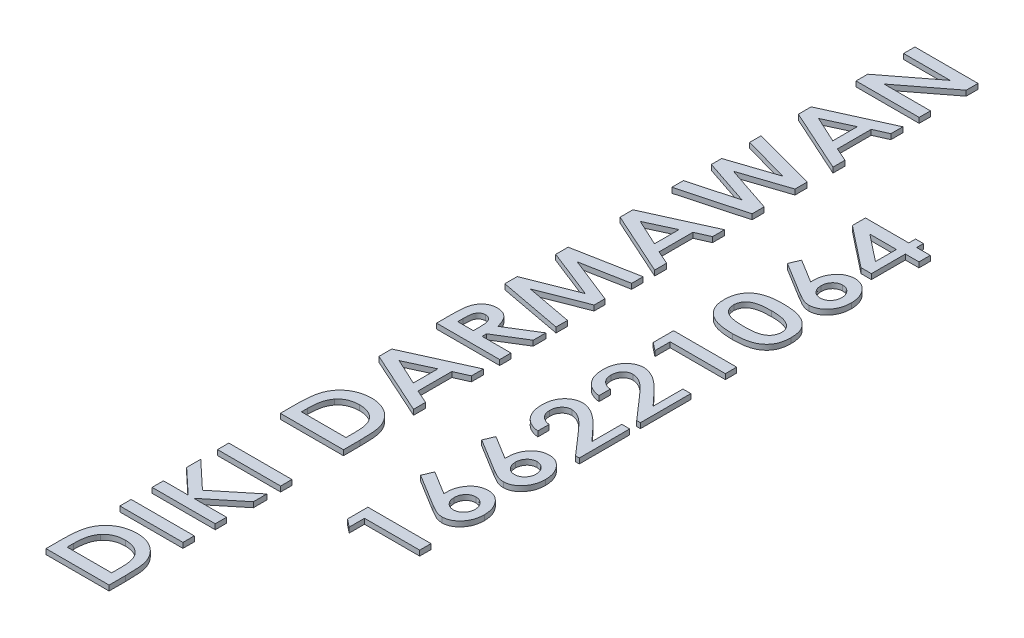
SolidWorks part; units mm, degrees
ref_plane "Front Plane" through (0, 0, 0) normal (0, 0, 1) x (1, 0, 0)
ref_plane "Top Plane" through (0, 0, 0) normal (0, 1, 0) x (1, 0, 0)
ref_plane "Right Plane" through (0, 0, 0) normal (1, 0, 0) x (0, 0, -1)
sketch "Sketch2" plane through (0, 0, 0) normal (0, 1, 0) x (1, 0, 0)
  line L0 (-33.5158, 51.9553) -> (-33.5158, -40.0447) construction
  text T0 "<b>DIKI DARMAWAN</b>\r\n<b>166221064</b>\r\n" font "Century Gothic" height in points 24
extrude "Boss-Extrude1" add sketch "Sketch2" along normal blind 0.5
sketch "Sketch7" plane through (0, 0.5, 0) normal (0, 1, 0) x (1, 0, 0)
  line L0 (-39.8658, 41.9793) -> (-33.5158, 41.9793) construction
  line L1 (-33.5158, 41.9793) -> (-33.5158, 43.3633) construction
  line L2 (-33.5158, 43.3633) -> (-37.6817, 43.3633) construction
  line L3 (-39.8658, -35.6861) -> (-33.5158, -35.6861)
  line L4 (-33.5158, -35.6861) -> (-33.5158, -33.9701)
  line L5 (-39.8658, -33.9955) -> (-39.8658, -35.6861)
  line L6 (-39.8658, -35.6861) -> (-33.5158, -35.6861)
  line L7 (-33.5158, -35.6861) -> (-33.5158, -33.9701)
  line L8 (-39.8658, -33.9955) -> (-39.8658, -35.6861)
  line L9 (-37.6817, 43.3633) -> (-33.5158, 46.5676) construction
  line L10 (-33.5158, 46.5676) -> (-33.5158, 47.9223) construction
  line L11 (-33.5158, 47.9223) -> (-39.8658, 47.9223) construction
  line L12 (-39.8658, 47.9223) -> (-39.8658, 46.5383) construction
  line L13 (-39.8658, 46.5383) -> (-35.6872, 46.5383) construction
  line L14 (-35.6872, 46.5383) -> (-39.8658, 43.3226) construction
  line L15 (-39.8658, 43.3226) -> (-39.8658, 41.9793) construction
  line L16 (-39.8658, 36.5058) -> (-33.5158, 33.6348) construction
  line L17 (-33.5158, 33.6348) -> (-33.5158, 35.1154) construction
  line L18 (-33.5158, 35.1154) -> (-34.8184, 35.6929) construction
  line L19 (-34.8184, 35.6929) -> (-34.8184, 38.742) construction
  line L20 (-34.8184, 38.742) -> (-33.5158, 39.3195) construction
  line L21 (-33.5158, 39.3195) -> (-33.5158, 40.7989) construction
  line L22 (-33.5158, 40.7989) -> (-39.8658, 37.9254) construction
  line L23 (-39.8658, 37.9254) -> (-39.8658, 36.5058) construction
  line L24 (-39.8658, 24.2726) -> (-33.5158, 25.9975) construction
  line L25 (-33.5158, 25.9975) -> (-33.5158, 27.3789) construction
  line L26 (-33.5158, 27.3789) -> (-37.6207, 28.7502) construction
  line L27 (-37.6207, 28.7502) -> (-33.5158, 30.1176) construction
  line L28 (-33.5158, 30.1176) -> (-33.5158, 31.5067) construction
  line L29 (-33.5158, 31.5067) -> (-39.8658, 33.2277) construction
  line L30 (-39.8658, 33.2277) -> (-39.8658, 31.8018) construction
  line L31 (-39.8658, 31.8018) -> (-35.8119, 30.704) construction
  line L32 (-35.8119, 30.704) -> (-39.8658, 29.3544) construction
  line L33 (-39.8658, 29.3544) -> (-39.8658, 28.151) construction
  line L34 (-39.8658, 28.151) -> (-35.8119, 26.7963) construction
  line L35 (-35.8119, 26.7963) -> (-39.8658, 25.696) construction
  line L36 (-39.8658, 25.696) -> (-39.8658, 24.2726) construction
  line L37 (-39.8658, 19.4096) -> (-33.5158, 16.5386) construction
  line L38 (-33.5158, 16.5386) -> (-33.5158, 18.0193) construction
  line L39 (-33.5158, 18.0193) -> (-34.8184, 18.5968) construction
  line L40 (-34.8184, 18.5968) -> (-34.8184, 21.6458) construction
  line L41 (-34.8184, 21.6458) -> (-33.5158, 22.2234) construction
  line L42 (-33.5158, 22.2234) -> (-33.5158, 23.7027) construction
  line L43 (-33.5158, 23.7027) -> (-39.8658, 20.8292) construction
  line L44 (-39.8658, 20.8292) -> (-39.8658, 19.4096) construction
  line L45 (-39.8658, 8.3276) -> (-33.5158, 7.1357) construction
  line L46 (-33.5158, 7.1357) -> (-33.5158, 8.5401) construction
  line L47 (-33.5158, 8.5401) -> (-37.5266, 9.2931) construction
  line L48 (-37.5266, 9.2931) -> (-33.5158, 10.8679) construction
  line L49 (-33.5158, 10.8679) -> (-33.5158, 12.1081) construction
  line L50 (-33.5158, 12.1081) -> (-37.5266, 13.6893) construction
  line L51 (-37.5266, 13.6893) -> (-33.5158, 14.4449) construction
  line L52 (-33.5158, 14.4449) -> (-33.5158, 15.8466) construction
  line L53 (-33.5158, 15.8466) -> (-39.8658, 14.6497) construction
  line L54 (-39.8658, 14.6497) -> (-39.8658, 13.2352) construction
  line L55 (-39.8658, 13.2352) -> (-35.4366, 11.4912) construction
  line L56 (-35.4366, 11.4912) -> (-39.8658, 9.751) construction
  line L57 (-39.8658, 9.751) -> (-39.8658, 8.3276) construction
  line L58 (-28.0383, 29.881) -> (-24.0263, 26.7149) construction
  line L59 (-24.0263, 26.7149) -> (-22.828, 26.7149) construction
  line L60 (-22.828, 26.7149) -> (-22.828, 29.9713) construction
  line L61 (-22.828, 29.9713) -> (-21.5254, 29.9713) construction
  line L62 (-21.5254, 29.9713) -> (-21.5254, 31.3553) construction
  line L63 (-21.5254, 31.3553) -> (-22.828, 31.3553) construction
  line L64 (-22.828, 31.3553) -> (-22.828, 32.0066) construction
  line L65 (-22.828, 32.0066) -> (-23.8863, 32.0066) construction
  line L66 (-23.8863, 32.0066) -> (-23.8863, 31.3553) construction
  line L67 (-23.8863, 31.3553) -> (-28.0383, 31.3553) construction
  line L68 (-28.0383, 31.3553) -> (-28.0383, 29.881) construction
  line L69 (-28.0383, 23.6226) -> (-24.8684, 21.6789) construction
  line L70 (-25.3517, 23.5335) -> (-27.5155, 24.8616) construction
  line L71 (-27.5155, 24.8616) -> (-28.0383, 23.6226) construction
  line L72 (-27.8754, 10.6211) -> (-26.8171, 9.7816) construction
  line L73 (-26.8171, 9.7816) -> (-26.8171, 11.4098) construction
  line L74 (-26.8171, 11.4098) -> (-21.5254, 11.4098) construction
  line L75 (-21.5254, 11.4098) -> (-21.5254, 12.7938) construction
  line L76 (-21.5254, 12.7938) -> (-27.8754, 12.7938) construction
  line L77 (-27.8754, 12.7938) -> (-27.8754, 10.6211) construction
  line L78 (-24.1039, 5.5559) -> (-22.103, 3.2688) construction
  line L79 (-22.103, 3.2688) -> (-21.5254, 3.2688) construction
  line L80 (-21.5254, 3.2688) -> (-21.5254, 8.3976) construction
  line L81 (-21.5254, 8.3976) -> (-22.5838, 8.3976) construction
  line L82 (-22.5838, 8.3976) -> (-22.5838, 5.7721) construction
  line L83 (-22.5838, 5.7721) -> (-23.3432, 6.5926) construction
  line L84 (-25.7588, 3.513) -> (-25.7588, 4.897) construction
  line L85 (-39.8658, 1.7627) -> (-33.5158, 1.7627) construction
  line L86 (-33.5158, 1.7627) -> (-33.5158, 3.1466) construction
  line L87 (-33.5158, 3.1466) -> (-36.2838, 3.1466) construction
  line L88 (-36.2838, 3.1466) -> (-36.2838, 3.3336) construction
  line L89 (-36.2838, 3.3336) -> (-33.5158, 5.0458) construction
  line L90 (-33.5158, 5.0458) -> (-33.5158, 6.6066) construction
  line L91 (-33.5158, 6.6066) -> (-36.4135, 4.8143) construction
  line L92 (-39.8658, 3.284) -> (-39.8658, 1.7627) construction
  line L93 (-24.1039, -0.3057) -> (-22.103, -2.5928) construction
  line L94 (-22.103, -2.5928) -> (-21.5254, -2.5928) construction
  line L95 (-21.5254, -2.5928) -> (-21.5254, 2.5361) construction
  line L96 (-21.5254, 2.5361) -> (-22.5838, 2.5361) construction
  line L97 (-22.5838, 2.5361) -> (-22.5838, -0.0894) construction
  line L98 (-22.5838, -0.0894) -> (-23.3432, 0.731) construction
  line L99 (-25.7588, -2.3486) -> (-25.7588, -0.9646) construction
  line L100 (-28.0383, -11.5466) -> (-24.8684, -13.4903) construction
  line L101 (-25.3517, -11.6357) -> (-27.5155, -10.3077) construction
  line L102 (-27.5155, -10.3077) -> (-28.0383, -11.5466) construction
  line L103 (-39.8658, -13.2168) -> (-33.5158, -13.2168) construction
  line L104 (-33.5158, -13.2168) -> (-33.5158, -11.5008) construction
  line L105 (-39.8658, -11.5263) -> (-39.8658, -13.2168) construction
  line L106 (-39.8658, -3.7109) -> (-33.5158, -6.5819) construction
  line L107 (-33.5158, -6.5819) -> (-33.5158, -5.1012) construction
  line L108 (-33.5158, -5.1012) -> (-34.8184, -4.5237) construction
  line L109 (-34.8184, -4.5237) -> (-34.8184, -1.4747) construction
  line L110 (-34.8184, -1.4747) -> (-33.5158, -0.8972) construction
  line L111 (-33.5158, -0.8972) -> (-33.5158, 0.5822) construction
  line L112 (-33.5158, 0.5822) -> (-39.8658, -2.2913) construction
  line L113 (-39.8658, -2.2913) -> (-39.8658, -3.7109) construction
  line L114 (-28.0383, -5.6851) -> (-24.8684, -7.6288) construction
  line L115 (-25.3517, -5.7741) -> (-27.5155, -4.4461) construction
  line L116 (-27.5155, -4.4461) -> (-28.0383, -5.6851) construction
  line L117 (-27.8754, -18.6866) -> (-26.8171, -19.5261) construction
  line L118 (-26.8171, -19.5261) -> (-26.8171, -17.8979) construction
  line L119 (-26.8171, -17.8979) -> (-21.5254, -17.8979) construction
  line L120 (-21.5254, -17.8979) -> (-21.5254, -16.5139) construction
  line L121 (-21.5254, -16.5139) -> (-27.8754, -16.5139) construction
  line L122 (-27.8754, -16.5139) -> (-27.8754, -18.6866) construction
  line L123 (-39.8658, -19.2412) -> (-33.5158, -19.2412) construction
  line L124 (-33.5158, -19.2412) -> (-33.5158, -17.8572) construction
  line L125 (-33.5158, -17.8572) -> (-39.8658, -17.8572) construction
  line L126 (-39.8658, -17.8572) -> (-39.8658, -19.2412) construction
  line L127 (-39.8658, -25.5098) -> (-33.5158, -25.5098) construction
  line L128 (-33.5158, -25.5098) -> (-33.5158, -24.1258) construction
  line L129 (-33.5158, -24.1258) -> (-36.3944, -24.1258) construction
  line L130 (-36.3944, -24.1258) -> (-33.5158, -21.7763) construction
  line L131 (-33.5158, -21.7763) -> (-33.5158, -20.096) construction
  line L132 (-33.5158, -20.096) -> (-37.0572, -22.9873) construction
  line L133 (-37.0572, -22.9873) -> (-39.8658, -20.3529) construction
  line L134 (-39.8658, -20.3529) -> (-39.8658, -22.1173) construction
  line L135 (-39.8658, -22.1173) -> (-37.725, -24.1258) construction
  line L136 (-37.725, -24.1258) -> (-39.8658, -24.1258) construction
  line L137 (-39.8658, -24.1258) -> (-39.8658, -25.5098) construction
  line L138 (-39.8658, -28.6034) -> (-33.5158, -28.6034) construction
  line L139 (-33.5158, -28.6034) -> (-33.5158, -27.2194) construction
  line L140 (-33.5158, -27.2194) -> (-39.8658, -27.2194) construction
  line L141 (-39.8658, -27.2194) -> (-39.8658, -28.6034) construction
  line L142 (-39.8658, 41.9793) -> (-33.5158, 41.9793)
  line L143 (-33.5158, 41.9793) -> (-33.5158, 43.3633)
  line L144 (-33.5158, 43.3633) -> (-37.6817, 43.3633)
  line L145 (-37.6817, 43.3633) -> (-33.5158, 46.5676)
  line L146 (-33.5158, 46.5676) -> (-33.5158, 47.9223)
  line L147 (-33.5158, 47.9223) -> (-39.8658, 47.9223)
  line L148 (-39.8658, 47.9223) -> (-39.8658, 46.5383)
  line L149 (-39.8658, 46.5383) -> (-35.6872, 46.5383)
  line L150 (-35.6872, 46.5383) -> (-39.8658, 43.3226)
  line L151 (-39.8658, 43.3226) -> (-39.8658, 41.9793)
  line L152 (-39.8658, 36.5058) -> (-33.5158, 33.6348)
  line L153 (-33.5158, 33.6348) -> (-33.5158, 35.1154)
  line L154 (-33.5158, 35.1154) -> (-34.8184, 35.6929)
  line L155 (-34.8184, 35.6929) -> (-34.8184, 38.742)
  line L156 (-34.8184, 38.742) -> (-33.5158, 39.3195)
  line L157 (-33.5158, 39.3195) -> (-33.5158, 40.7989)
  line L158 (-33.5158, 40.7989) -> (-39.8658, 37.9254)
  line L159 (-39.8658, 37.9254) -> (-39.8658, 36.5058)
  line L160 (-39.8658, 24.2726) -> (-33.5158, 25.9975)
  line L161 (-33.5158, 25.9975) -> (-33.5158, 27.3789)
  line L162 (-33.5158, 27.3789) -> (-37.6207, 28.7502)
  line L163 (-37.6207, 28.7502) -> (-33.5158, 30.1176)
  line L164 (-33.5158, 30.1176) -> (-33.5158, 31.5067)
  line L165 (-33.5158, 31.5067) -> (-39.8658, 33.2277)
  line L166 (-39.8658, 33.2277) -> (-39.8658, 31.8018)
  line L167 (-39.8658, 31.8018) -> (-35.8119, 30.704)
  line L168 (-35.8119, 30.704) -> (-39.8658, 29.3544)
  line L169 (-39.8658, 29.3544) -> (-39.8658, 28.151)
  line L170 (-39.8658, 28.151) -> (-35.8119, 26.7963)
  line L171 (-35.8119, 26.7963) -> (-39.8658, 25.696)
  line L172 (-39.8658, 25.696) -> (-39.8658, 24.2726)
  line L173 (-39.8658, 19.4096) -> (-33.5158, 16.5386)
  line L174 (-33.5158, 16.5386) -> (-33.5158, 18.0193)
  line L175 (-33.5158, 18.0193) -> (-34.8184, 18.5968)
  line L176 (-34.8184, 18.5968) -> (-34.8184, 21.6458)
  line L177 (-34.8184, 21.6458) -> (-33.5158, 22.2234)
  line L178 (-33.5158, 22.2234) -> (-33.5158, 23.7027)
  line L179 (-33.5158, 23.7027) -> (-39.8658, 20.8292)
  line L180 (-39.8658, 20.8292) -> (-39.8658, 19.4096)
  line L181 (-39.8658, 8.3276) -> (-33.5158, 7.1357)
  line L182 (-33.5158, 7.1357) -> (-33.5158, 8.5401)
  line L183 (-33.5158, 8.5401) -> (-37.5266, 9.2931)
  line L184 (-37.5266, 9.2931) -> (-33.5158, 10.8679)
  line L185 (-33.5158, 10.8679) -> (-33.5158, 12.1081)
  line L186 (-33.5158, 12.1081) -> (-37.5266, 13.6893)
  line L187 (-37.5266, 13.6893) -> (-33.5158, 14.4449)
  line L188 (-33.5158, 14.4449) -> (-33.5158, 15.8466)
  line L189 (-33.5158, 15.8466) -> (-39.8658, 14.6497)
  line L190 (-39.8658, 14.6497) -> (-39.8658, 13.2352)
  line L191 (-39.8658, 13.2352) -> (-35.4366, 11.4912)
  line L192 (-35.4366, 11.4912) -> (-39.8658, 9.751)
  line L193 (-39.8658, 9.751) -> (-39.8658, 8.3276)
  line L194 (-28.0383, 29.881) -> (-24.0263, 26.7149)
  line L195 (-24.0263, 26.7149) -> (-22.828, 26.7149)
  line L196 (-22.828, 26.7149) -> (-22.828, 29.9713)
  line L197 (-22.828, 29.9713) -> (-21.5254, 29.9713)
  line L198 (-21.5254, 29.9713) -> (-21.5254, 31.3553)
  line L199 (-21.5254, 31.3553) -> (-22.828, 31.3553)
  line L200 (-22.828, 31.3553) -> (-22.828, 32.0066)
  line L201 (-22.828, 32.0066) -> (-23.8863, 32.0066)
  line L202 (-23.8863, 32.0066) -> (-23.8863, 31.3553)
  line L203 (-23.8863, 31.3553) -> (-28.0383, 31.3553)
  line L204 (-28.0383, 31.3553) -> (-28.0383, 29.881)
  line L205 (-28.0383, 23.6226) -> (-24.8684, 21.6789)
  line L206 (-25.3517, 23.5335) -> (-27.5155, 24.8616)
  line L207 (-27.5155, 24.8616) -> (-28.0383, 23.6226)
  line L208 (-27.8754, 10.6211) -> (-26.8171, 9.7816)
  line L209 (-26.8171, 9.7816) -> (-26.8171, 11.4098)
  line L210 (-26.8171, 11.4098) -> (-21.5254, 11.4098)
  line L211 (-21.5254, 11.4098) -> (-21.5254, 12.7938)
  line L212 (-21.5254, 12.7938) -> (-27.8754, 12.7938)
  line L213 (-27.8754, 12.7938) -> (-27.8754, 10.6211)
  line L214 (-24.1039, 5.5559) -> (-22.103, 3.2688)
  line L215 (-22.103, 3.2688) -> (-21.5254, 3.2688)
  line L216 (-21.5254, 3.2688) -> (-21.5254, 8.3976)
  line L217 (-21.5254, 8.3976) -> (-22.5838, 8.3976)
  line L218 (-22.5838, 8.3976) -> (-22.5838, 5.7721)
  line L219 (-22.5838, 5.7721) -> (-23.3432, 6.5926)
  line L220 (-25.7588, 3.513) -> (-25.7588, 4.897)
  line L221 (-39.8658, 1.7627) -> (-33.5158, 1.7627)
  line L222 (-33.5158, 1.7627) -> (-33.5158, 3.1466)
  line L223 (-33.5158, 3.1466) -> (-36.2838, 3.1466)
  line L224 (-36.2838, 3.1466) -> (-36.2838, 3.3336)
  line L225 (-36.2838, 3.3336) -> (-33.5158, 5.0458)
  line L226 (-33.5158, 5.0458) -> (-33.5158, 6.6066)
  line L227 (-33.5158, 6.6066) -> (-36.4135, 4.8143)
  line L228 (-39.8658, 3.284) -> (-39.8658, 1.7627)
  line L229 (-24.1039, -0.3057) -> (-22.103, -2.5928)
  line L230 (-22.103, -2.5928) -> (-21.5254, -2.5928)
  line L231 (-21.5254, -2.5928) -> (-21.5254, 2.5361)
  line L232 (-21.5254, 2.5361) -> (-22.5838, 2.5361)
  line L233 (-22.5838, 2.5361) -> (-22.5838, -0.0894)
  line L234 (-22.5838, -0.0894) -> (-23.3432, 0.731)
  line L235 (-25.7588, -2.3486) -> (-25.7588, -0.9646)
  line L236 (-28.0383, -11.5466) -> (-24.8684, -13.4903)
  line L237 (-25.3517, -11.6357) -> (-27.5155, -10.3077)
  line L238 (-27.5155, -10.3077) -> (-28.0383, -11.5466)
  line L239 (-39.8658, -13.2168) -> (-33.5158, -13.2168)
  line L240 (-33.5158, -13.2168) -> (-33.5158, -11.5008)
  line L241 (-39.8658, -11.5263) -> (-39.8658, -13.2168)
  line L242 (-39.8658, -3.7109) -> (-33.5158, -6.5819)
  line L243 (-33.5158, -6.5819) -> (-33.5158, -5.1012)
  line L244 (-33.5158, -5.1012) -> (-34.8184, -4.5237)
  line L245 (-34.8184, -4.5237) -> (-34.8184, -1.4747)
  line L246 (-34.8184, -1.4747) -> (-33.5158, -0.8972)
  line L247 (-33.5158, -0.8972) -> (-33.5158, 0.5822)
  line L248 (-33.5158, 0.5822) -> (-39.8658, -2.2913)
  line L249 (-39.8658, -2.2913) -> (-39.8658, -3.7109)
  line L250 (-28.0383, -5.6851) -> (-24.8684, -7.6288)
  line L251 (-25.3517, -5.7741) -> (-27.5155, -4.4461)
  line L252 (-27.5155, -4.4461) -> (-28.0383, -5.6851)
  line L253 (-27.8754, -18.6866) -> (-26.8171, -19.5261)
  line L254 (-26.8171, -19.5261) -> (-26.8171, -17.8979)
  line L255 (-26.8171, -17.8979) -> (-21.5254, -17.8979)
  line L256 (-21.5254, -17.8979) -> (-21.5254, -16.5139)
  line L257 (-21.5254, -16.5139) -> (-27.8754, -16.5139)
  line L258 (-27.8754, -16.5139) -> (-27.8754, -18.6866)
  line L259 (-39.8658, -19.2412) -> (-33.5158, -19.2412)
  line L260 (-33.5158, -19.2412) -> (-33.5158, -17.8572)
  line L261 (-33.5158, -17.8572) -> (-39.8658, -17.8572)
  line L262 (-39.8658, -17.8572) -> (-39.8658, -19.2412)
  line L263 (-39.8658, -25.5098) -> (-33.5158, -25.5098)
  line L264 (-33.5158, -25.5098) -> (-33.5158, -24.1258)
  line L265 (-33.5158, -24.1258) -> (-36.3944, -24.1258)
  line L266 (-36.3944, -24.1258) -> (-33.5158, -21.7763)
  line L267 (-33.5158, -21.7763) -> (-33.5158, -20.096)
  line L268 (-33.5158, -20.096) -> (-37.0572, -22.9873)
  line L269 (-37.0572, -22.9873) -> (-39.8658, -20.3529)
  line L270 (-39.8658, -20.3529) -> (-39.8658, -22.1173)
  line L271 (-39.8658, -22.1173) -> (-37.725, -24.1258)
  line L272 (-37.725, -24.1258) -> (-39.8658, -24.1258)
  line L273 (-39.8658, -24.1258) -> (-39.8658, -25.5098)
  line L274 (-39.8658, -28.6034) -> (-33.5158, -28.6034)
  line L275 (-33.5158, -28.6034) -> (-33.5158, -27.2194)
  line L276 (-33.5158, -27.2194) -> (-39.8658, -27.2194)
  line L277 (-39.8658, -27.2194) -> (-39.8658, -28.6034)
  line L278 (-39.7158, -35.5361) -> (-33.6658, -35.5361)
  line L279 (-33.6658, -35.5361) -> (-33.6658, -33.9703)
  line L280 (-39.7158, -33.9964) -> (-39.7158, -35.5361)
  line L281 (-39.7158, 42.1293) -> (-33.6658, 42.1293)
  line L282 (-33.6658, 42.1293) -> (-33.6658, 43.2133)
  line L283 (-33.6658, 43.2133) -> (-38.1228, 43.2133)
  line L284 (-38.1228, 43.2133) -> (-33.6658, 46.6414)
  line L285 (-33.6658, 46.6414) -> (-33.6658, 47.7723)
  line L286 (-33.6658, 47.7723) -> (-39.7158, 47.7723)
  line L287 (-39.7158, 47.7723) -> (-39.7158, 46.6883)
  line L288 (-39.7158, 46.6883) -> (-35.2463, 46.6883)
  line L289 (-35.2463, 46.6883) -> (-39.7158, 43.2488)
  line L290 (-39.7158, 43.2488) -> (-39.7158, 42.1293)
  line L291 (-39.7158, 36.6026) -> (-33.6658, 33.8672)
  line L292 (-33.6658, 33.8672) -> (-33.6658, 35.0179)
  line L293 (-33.6658, 35.0179) -> (-34.9684, 35.5954)
  line L294 (-34.9684, 35.5954) -> (-34.9684, 38.8396)
  line L295 (-34.9684, 38.8396) -> (-33.6658, 39.4171)
  line L296 (-33.6658, 39.4171) -> (-33.6658, 40.5664)
  line L297 (-33.6658, 40.5664) -> (-39.7158, 37.8286)
  line L298 (-39.7158, 37.8286) -> (-39.7158, 36.6026)
  line L299 (-39.7158, 24.4688) -> (-33.6658, 26.1122)
  line L300 (-33.6658, 26.1122) -> (-33.6658, 27.2709)
  line L301 (-33.6658, 27.2709) -> (-38.0947, 28.7504)
  line L302 (-38.0947, 28.7504) -> (-33.6658, 30.2257)
  line L303 (-33.6658, 30.2257) -> (-33.6658, 31.3919)
  line L304 (-33.6658, 31.3919) -> (-39.7158, 33.0317)
  line L305 (-39.7158, 33.0317) -> (-39.7158, 31.9166)
  line L306 (-39.7158, 31.9166) -> (-35.2926, 30.7188)
  line L307 (-35.2926, 30.7188) -> (-39.7158, 29.2462)
  line L308 (-39.7158, 29.2462) -> (-39.7158, 28.2591)
  line L309 (-39.7158, 28.2591) -> (-35.294, 26.7814)
  line L310 (-35.294, 26.7814) -> (-39.7158, 25.5813)
  line L311 (-39.7158, 25.5813) -> (-39.7158, 24.4688)
  line L312 (-39.7158, 19.5064) -> (-33.6658, 16.7711)
  line L313 (-33.6658, 16.7711) -> (-33.6658, 17.9217)
  line L314 (-33.6658, 17.9217) -> (-34.9684, 18.4992)
  line L315 (-34.9684, 18.4992) -> (-34.9684, 21.7434)
  line L316 (-34.9684, 21.7434) -> (-33.6658, 22.3209)
  line L317 (-33.6658, 22.3209) -> (-33.6658, 23.4702)
  line L318 (-33.6658, 23.4702) -> (-39.7158, 20.7324)
  line L319 (-39.7158, 20.7324) -> (-39.7158, 19.5064)
  line L320 (-39.7158, 8.4521) -> (-33.6658, 7.3165)
  line L321 (-33.6658, 7.3165) -> (-33.6658, 8.4156)
  line L322 (-33.6658, 8.4156) -> (-38.0672, 9.242)
  line L323 (-38.0672, 9.242) -> (-33.6658, 10.9701)
  line L324 (-33.6658, 10.9701) -> (-33.6658, 12.006)
  line L325 (-33.6658, 12.006) -> (-38.0653, 13.7404)
  line L326 (-38.0653, 13.7404) -> (-33.6658, 14.5692)
  line L327 (-33.6658, 14.5692) -> (-33.6658, 15.6657)
  line L328 (-33.6658, 15.6657) -> (-39.7158, 14.5253)
  line L329 (-39.7158, 14.5253) -> (-39.7158, 13.3373)
  line L330 (-39.7158, 13.3373) -> (-35.0268, 11.491)
  line L331 (-35.0268, 11.491) -> (-39.7158, 9.6488)
  line L332 (-39.7158, 9.6488) -> (-39.7158, 8.4521)
  line L333 (-27.8883, 29.9537) -> (-23.9742, 26.8649)
  line L334 (-23.9742, 26.8649) -> (-22.978, 26.8649)
  line L335 (-22.978, 26.8649) -> (-22.978, 30.1213)
  line L336 (-22.978, 30.1213) -> (-21.6754, 30.1213)
  line L337 (-21.6754, 30.1213) -> (-21.6754, 31.2053)
  line L338 (-21.6754, 31.2053) -> (-22.978, 31.2053)
  line L339 (-22.978, 31.2053) -> (-22.978, 31.8566)
  line L340 (-22.978, 31.8566) -> (-23.7363, 31.8566)
  line L341 (-23.7363, 31.8566) -> (-23.7363, 31.2053)
  line L342 (-23.7363, 31.2053) -> (-27.8883, 31.2053)
  line L343 (-27.8883, 31.2053) -> (-27.8883, 29.9537)
  line L344 (-27.8499, 23.6831) -> (-24.7911, 21.8075)
  line L345 (-25.2073, 23.2689) -> (-27.4451, 24.6424)
  line L346 (-27.4451, 24.6424) -> (-27.8499, 23.6831)
  line L347 (-27.7254, 10.6936) -> (-26.9671, 10.092)
  line L348 (-26.9671, 10.092) -> (-26.9671, 11.5598)
  line L349 (-26.9671, 11.5598) -> (-21.6754, 11.5598)
  line L350 (-21.6754, 11.5598) -> (-21.6754, 12.6438)
  line L351 (-21.6754, 12.6438) -> (-27.7254, 12.6438)
  line L352 (-27.7254, 12.6438) -> (-27.7254, 10.6936)
  line L353 (-23.991, 5.6546) -> (-22.0349, 3.4188)
  line L354 (-22.0349, 3.4188) -> (-21.6754, 3.4188)
  line L355 (-21.6754, 3.4188) -> (-21.6754, 8.2476)
  line L356 (-21.6754, 8.2476) -> (-22.4338, 8.2476)
  line L357 (-22.4338, 8.2476) -> (-22.4338, 5.3892)
  line L358 (-22.4338, 5.3892) -> (-23.4534, 6.4908)
  line L359 (-25.9088, 3.6759) -> (-25.9088, 4.7573)
  line L360 (-39.7158, 1.9127) -> (-33.6658, 1.9127)
  line L361 (-33.6658, 1.9127) -> (-33.6658, 2.9966)
  line L362 (-33.6658, 2.9966) -> (-36.4338, 2.9966)
  line L363 (-36.4338, 2.9966) -> (-36.4338, 3.4172)
  line L364 (-36.4338, 3.4172) -> (-33.6658, 5.1294)
  line L365 (-33.6658, 5.1294) -> (-33.6658, 6.3374)
  line L366 (-33.6658, 6.3374) -> (-36.4991, 4.585)
  line L367 (-39.7158, 3.2838) -> (-39.7158, 1.9127)
  line L368 (-23.991, -0.2068) -> (-22.0349, -2.4428)
  line L369 (-22.0349, -2.4428) -> (-21.6754, -2.4428)
  line L370 (-21.6754, -2.4428) -> (-21.6754, 2.3861)
  line L371 (-21.6754, 2.3861) -> (-22.4338, 2.3861)
  line L372 (-22.4338, 2.3861) -> (-22.4338, -0.4723)
  line L373 (-22.4338, -0.4723) -> (-23.4533, 0.6292)
  line L374 (-25.9088, -2.1856) -> (-25.9088, -1.1042)
  line L375 (-27.8499, -11.4862) -> (-24.7911, -13.3617)
  line L376 (-25.2073, -11.9003) -> (-27.4451, -10.5268)
  line L377 (-27.4451, -10.5268) -> (-27.8499, -11.4862)
  line L378 (-39.7158, -13.0668) -> (-33.6658, -13.0668)
  line L379 (-33.6658, -13.0668) -> (-33.6658, -11.5011)
  line L380 (-39.7158, -11.5272) -> (-39.7158, -13.0668)
  line L381 (-39.7158, -3.6141) -> (-33.6658, -6.3494)
  line L382 (-33.6658, -6.3494) -> (-33.6658, -5.1988)
  line L383 (-33.6658, -5.1988) -> (-34.9684, -4.6213)
  line L384 (-34.9684, -4.6213) -> (-34.9684, -1.3771)
  line L385 (-34.9684, -1.3771) -> (-33.6658, -0.7996)
  line L386 (-33.6658, -0.7996) -> (-33.6658, 0.3497)
  line L387 (-33.6658, 0.3497) -> (-39.7158, -2.3881)
  line L388 (-39.7158, -2.3881) -> (-39.7158, -3.6141)
  line L389 (-27.8499, -5.6246) -> (-24.7911, -7.5002)
  line L390 (-25.2073, -6.0388) -> (-27.4451, -4.6653)
  line L391 (-27.4451, -4.6653) -> (-27.8499, -5.6246)
  line L392 (-27.7254, -18.6141) -> (-26.9671, -19.2157)
  line L393 (-26.9671, -19.2157) -> (-26.9671, -17.7479)
  line L394 (-26.9671, -17.7479) -> (-21.6754, -17.7479)
  line L395 (-21.6754, -17.7479) -> (-21.6754, -16.6639)
  line L396 (-21.6754, -16.6639) -> (-27.7254, -16.6639)
  line L397 (-27.7254, -16.6639) -> (-27.7254, -18.6141)
  line L398 (-39.7158, -19.0912) -> (-33.6658, -19.0912)
  line L399 (-33.6658, -19.0912) -> (-33.6658, -18.0072)
  line L400 (-33.6658, -18.0072) -> (-39.7158, -18.0072)
  line L401 (-39.7158, -18.0072) -> (-39.7158, -19.0912)
  line L402 (-39.7158, -25.3598) -> (-33.6658, -25.3598)
  line L403 (-33.6658, -25.3598) -> (-33.6658, -24.2758)
  line L404 (-33.6658, -24.2758) -> (-36.8155, -24.2758)
  line L405 (-36.8155, -24.2758) -> (-33.6658, -21.7052)
  line L406 (-33.6658, -21.7052) -> (-33.6658, -20.4121)
  line L407 (-33.6658, -20.4121) -> (-37.064, -23.1866)
  line L408 (-37.064, -23.1866) -> (-39.7158, -20.6993)
  line L409 (-39.7158, -20.6993) -> (-39.7158, -22.0523)
  line L410 (-39.7158, -22.0523) -> (-37.3459, -24.2758)
  line L411 (-37.3459, -24.2758) -> (-39.7158, -24.2758)
  line L412 (-39.7158, -24.2758) -> (-39.7158, -25.3598)
  line L413 (-39.7158, -28.4534) -> (-33.6658, -28.4534)
  line L414 (-33.6658, -28.4534) -> (-33.6658, -27.3694)
  line L415 (-33.6658, -27.3694) -> (-39.7158, -27.3694)
  line L416 (-39.7158, -27.3694) -> (-39.7158, -28.4534)
  spline S0 degree 3 poles (-1808.6128, -2389.1531) (-78.8253, 59.5496) (-53.2377, 38.3496) (-24.5809, 21.5099) (-24.4502, 21.4375) (-24.3292, 21.3745) (-24.2197, 21.3174) (-24.1195, 21.2704) (-24.029, 21.2323) (-23.9232, 21.1912) (-23.7964, 21.1552) (-23.6472, 21.1207) (-18.2819, 20.4284) (-11.2342, 49.1738) (-183.9616, -2974.3609) knots -60.154759 -60.154759 -60.154759 -60.154759 0.106469 0.204611 0.295393 0.378181 0.452678 0.519951 0.579391 0.631381 0.726298 0.818725 0.909691 10.542763 10.542763 10.542763 10.542763 only from (-24.8684, 21.6789) to (-23.3483, 21.0976) construction
  spline S1 degree 3 poles (209.82, -2969.7503) (-37.257, 55.4092) (-28.6304, 20.1474) (-22.9687, 21.1359) (-22.7868, 21.19) (-22.61, 21.2642) (-22.4388, 21.3601) (-22.2743, 21.4786) (-22.1145, 21.6168) (-21.9626, 21.7743) (-21.8216, 21.947) (-21.6995, 22.1339) (-21.5942, 22.3305) (-21.5087, 22.5384) (-21.4442, 22.7574) (-21.3975, 22.9859) (-20.4519, 30.327) (-55.9687, 39.8605) (2973.9814, -141.5285) knots -4.842079 -4.842079 -4.842079 -4.842079 0.056071 0.111363 0.166273 0.221781 0.278723 0.337476 0.398732 0.463243 0.528625 0.593419 0.658114 0.723463 0.789632 0.85741 0.927275 7.250916 7.250916 7.250916 7.250916 only from (-23.3483, 21.0976) to (-21.3626, 23.4712) construction
  spline S2 degree 3 poles (3966.1757, -34.3646) (-60.9604, -68.1646) (-33.0925, -50.6053) (-33.5251, -33.3047) (-33.536, -33.0083) (-33.5517, -32.7388) (-33.5749, -32.4967) (-33.6014, -32.2816) (-33.6304, -32.0927) (-33.6798, -31.8778) (-33.7589, -31.6308) (-33.8844, -31.3493) (-34.0419, -31.079) (-34.2286, -30.821) (-34.4433, -30.581) (-34.6869, -30.3668) (-34.9577, -30.1816) (-35.2023, -30.0513) (-35.4084, -29.9613) (-35.5683, -29.9033) (-35.7317, -29.8535) (-35.8985, -29.8122) (-36.0695, -29.7827) (-36.2434, -29.7589) (-44.8139, -29.17) (-54.2177, -58.2619) (58.3137, 3968.7086) knots -8.49979 -8.49979 -8.49979 -8.49979 0.058578 0.112501 0.161989 0.207067 0.247572 0.283716 0.315537 0.343185 0.393994 0.445109 0.497127 0.550321 0.604272 0.657959 0.712295 0.768126 0.796356 0.824824 0.853223 0.881844 0.910736 0.940062 0.969639 5.207567 5.207567 5.207567 5.207567 only from (-33.5158, -33.9701) to (-36.6018, -29.7431)
  spline S3 degree 3 poles (-199.7982, 3966.6799) (-17.3458, -68.216) (-28.1369, -28.8701) (-37.1003, -29.7719) (-37.3387, -29.8127) (-37.5694, -29.8682) (-37.7918, -29.9411) (-38.0055, -30.0303) (-38.2116, -30.1349) (-38.4073, -30.2556) (-38.5932, -30.3875) (-38.7658, -30.5304) (-38.927, -30.6803) (-39.0737, -30.8398) (-39.2063, -31.0085) (-39.3265, -31.1854) (-39.4319, -31.3721) (-39.5267, -31.569) (-39.6078, -31.7844) (-39.6769, -32.0231) (-39.7369, -32.2876) (-39.7821, -32.579) (-39.821, -32.8958) (-39.8463, -33.2392) (-40.5587, -48.4546) (-4.5448, -64.4387) (-4039.198, 17.6324) knots -4.291627 -4.291627 -4.291627 -4.291627 0.041612 0.081944 0.121399 0.160137 0.198216 0.236066 0.273641 0.311449 0.348728 0.385368 0.421269 0.456593 0.491541 0.526438 0.561365 0.59662 0.633545 0.674082 0.71843 0.766467 0.818625 0.874946 0.935317 8.288112 8.288112 8.288112 8.288112 only from (-36.6018, -29.7431) to (-39.8658, -33.9955)
  spline S4 degree 3 poles (-33.5158, -33.9701) (-33.5162, -33.853) (-33.517, -33.6283) (-33.5251, -33.3047) (-33.536, -33.0083) (-33.5517, -32.7388) (-33.5749, -32.4967) (-33.6014, -32.2816) (-33.6304, -32.0927) (-33.6798, -31.8778) (-33.7589, -31.6308) (-33.8844, -31.3493) (-34.0419, -31.079) (-34.2286, -30.821) (-34.4433, -30.581) (-34.6869, -30.3668) (-34.9577, -30.1816) (-35.2023, -30.0513) (-35.4084, -29.9613) (-35.5683, -29.9033) (-35.7317, -29.8535) (-35.8985, -29.8122) (-36.0695, -29.7827) (-36.2434, -29.7589) (-36.4214, -29.7467) (-36.5411, -29.7443) (-36.6018, -29.7431) knots 0 0 0 0 0.058578 0.112501 0.161989 0.207067 0.247572 0.283716 0.315537 0.343185 0.393994 0.445109 0.497127 0.550321 0.604272 0.657959 0.712295 0.768126 0.796356 0.824824 0.853223 0.881844 0.910736 0.940062 0.969639 1 1 1 1
  spline S5 degree 3 poles (-36.6018, -29.7431) (-36.6867, -29.7444) (-36.8538, -29.7471) (-37.1003, -29.7719) (-37.3387, -29.8127) (-37.5694, -29.8682) (-37.7918, -29.9411) (-38.0055, -30.0303) (-38.2116, -30.1349) (-38.4073, -30.2556) (-38.5932, -30.3875) (-38.7658, -30.5304) (-38.927, -30.6803) (-39.0737, -30.8398) (-39.2063, -31.0085) (-39.3265, -31.1854) (-39.4319, -31.3721) (-39.5267, -31.569) (-39.6078, -31.7844) (-39.6769, -32.0231) (-39.7369, -32.2876) (-39.7821, -32.579) (-39.821, -32.8958) (-39.8463, -33.2392) (-39.8636, -33.6086) (-39.8651, -33.8636) (-39.8658, -33.9955) knots 0 0 0 0 0.041612 0.081944 0.121399 0.160137 0.198216 0.236066 0.273641 0.311449 0.348728 0.385368 0.421269 0.456593 0.491541 0.526438 0.561365 0.59662 0.633545 0.674082 0.71843 0.766467 0.818625 0.874946 0.935317 1 1 1 1
  spline S6 degree 3 poles (2975.1398, 165.368) (-53.7607, 7.1437) (-20.5138, 16.4364) (-21.3947, 23.9384) (-21.4408, 24.1594) (-21.5027, 24.3728) (-21.5851, 24.5761) (-21.6823, 24.7721) (-21.8011, 24.9572) (-21.9343, 25.1324) (-22.0804, 25.2928) (-22.2361, 25.4343) (-22.4008, 25.5528) (-22.5726, 25.651) (-22.753, 25.7265) (-22.9418, 25.7796) (-28.715, 26.8023) (-37.6736, -9.6473) (219.0271, 3015.8131) knots -6.429509 -6.429509 -6.429509 -6.429509 0.070179 0.137781 0.204064 0.268629 0.332912 0.396807 0.460866 0.526074 0.590237 0.651515 0.710838 0.768305 0.825322 0.882352 0.940612 5.966602 5.966602 5.966602 5.966602 only from (-21.3626, 23.4712) to (-23.3394, 25.8194) construction
  spline S7 degree 3 poles (-249.4112, 3017.1382) (-8.651, -9.1777) (-17.674, 26.7826) (-23.7499, 25.7808) (-23.9437, 25.7293) (-24.129, 25.6559) (-24.3049, 25.5616) (-24.4718, 25.4455) (-24.6296, 25.3088) (-24.777, 25.1533) (-24.9114, 24.9834) (-25.0297, 24.8031) (-25.1303, 24.6135) (-25.2095, 24.4142) (-25.2741, 24.2069) (-25.3195, 23.9906) (-26.204, 16.6818) (7.181, 7.4249) (-3021.1983, 178.8828) knots -5.250008 -5.250008 -5.250008 -5.250008 0.061951 0.121941 0.180981 0.23906 0.297784 0.357079 0.418501 0.482164 0.546238 0.609895 0.672634 0.735728 0.799308 0.864475 0.930947 7.299873 7.299873 7.299873 7.299873 only from (-23.3394, 25.8194) to (-25.3517, 23.5335) construction
  spline S8 degree 3 poles (-3022.6082, -159.8984) (8.615, 36.4362) (-29.1493, 25.4846) (-27.9904, 17.0679) (-27.9234, 16.7963) (-27.8272, 16.5423) (-27.7065, 16.3043) (-27.5555, 16.0858) (-22.7816, 10.5606) (10.6141, 34.5234) (-2105.9818, -2147) knots -11.111746 -11.111746 -11.111746 -11.111746 0.137684 0.268389 0.394144 0.516527 0.636206 0.755441 0.876165 10.51565 10.51565 10.51565 10.51565 only from (-28.0383, 17.6555) to (-27.1746, 15.7042) construction
  spline S9 degree 3 poles (-1668.3136, -2495.4148) (-17.0367, 56.0309) (-32.9305, 18.6523) (-26.7166, 15.4209) (-26.4429, 15.3135) (-26.1399, 15.2244) (-25.8065, 15.157) (-25.4437, 15.1079) (-12.6546, 14.1644) (1.2281, 48.727) (-90.0314, -2983.9269) knots -7.560261 -7.560261 -7.560261 -7.560261 0.097241 0.200146 0.310265 0.428446 0.555909 0.693475 0.841181 15.009134 15.009134 15.009134 15.009134 only from (-27.1746, 15.7042) to (-24.6381, 15.0732) construction
  spline S10 degree 3 poles (23.7992, -2984.386) (-47.2725, 42.5311) (-35.3189, 14.4816) (-24.0534, 15.0914) (-23.7847, 15.1162) (-23.534, 15.1522) (-23.3007, 15.1951) (-23.0862, 15.2522) (-22.8884, 15.3153) (-22.7088, 15.3929) (-22.5441, 15.4794) (-22.3891, 15.5701) (-22.2464, 15.6714) (-22.1142, 15.7793) (-21.992, 15.894) (-21.8827, 16.0182) (-21.7832, 16.1496) (-21.6936, 16.2883) (-21.6162, 16.4361) (-21.5467, 16.5911) (-21.4903, 16.7557) (-21.4426, 16.9276) (-21.4079, 17.1081) (-21.3805, 17.2965) (-20.7867, 25.1429) (-47.8587, 33.81) (2977.5009, -55.1201) knots -6.86257 -6.86257 -6.86257 -6.86257 0.063279 0.122927 0.179035 0.23171 0.281033 0.327007 0.370204 0.410526 0.449007 0.486281 0.522564 0.558122 0.592765 0.627082 0.661285 0.695578 0.73004 0.765359 0.801527 0.838583 0.876638 0.91621 0.957366 5.784961 5.784961 5.784961 5.784961 only from (-24.6381, 15.0732) to (-21.3626, 17.6962) construction
  spline S11 degree 3 poles (2977.6081, 88.6822) (-47.9532, 1.6487) (-20.7861, 10.2748) (-21.3805, 18.0946) (-21.408, 18.2817) (-21.4421, 18.4602) (-21.4907, 18.6288) (-21.5451, 18.7896) (-21.6139, 18.9403) (-21.6907, 19.0836) (-21.7812, 19.2174) (-21.88, 19.3459) (-21.9932, 19.4652) (-22.1164, 19.5793) (-22.2534, 19.6839) (-22.3999, 19.7844) (-22.5597, 19.8751) (-22.7305, 19.9613) (-22.9164, 20.0383) (-23.1194, 20.104) (-23.3396, 20.1595) (-23.5774, 20.2052) (-23.8327, 20.2402) (-24.1056, 20.2654) (-35.5497, 20.8732) (-47.6285, -7.0825) (18.0103, 3019.731) knots -4.744814 -4.744814 -4.744814 -4.744814 0.042421 0.083108 0.122221 0.159827 0.195936 0.23109 0.265163 0.298756 0.331996 0.365401 0.399317 0.433993 0.469662 0.506263 0.54426 0.583722 0.625056 0.66912 0.716139 0.766041 0.819496 0.876109 0.936248 7.936329 7.936329 7.936329 7.936329 only from (-21.3626, 17.6962) to (-24.6979, 20.2835) construction
  spline S12 degree 3 poles (-84.1018, 3019.4842) (-2.3247, -7.6609) (-14.2057, 20.8875) (-25.2842, 20.2648) (-25.5552, 20.2422) (-25.8084, 20.2058) (-26.045, 20.1625) (-26.2634, 20.1061) (-26.4657, 20.042) (-26.6512, 19.9662) (-26.8225, 19.8822) (-26.9814, 19.7887) (-27.1283, 19.6868) (-27.2663, 19.5789) (-27.3903, 19.4595) (-27.506, 19.3343) (-27.6074, 19.1981) (-27.6996, 19.0557) (-27.7799, 18.905) (-27.8482, 18.7469) (-27.9068, 18.5824) (-27.9559, 18.411) (-27.9919, 18.2318) (-28.0185, 18.0458) (-28.6605, 10.911) (0.456, 2.5474) (-3025.9033, 126.8547) knots -6.671965 -6.671965 -6.671965 -6.671965 0.062582 0.121835 0.177822 0.230436 0.27973 0.326212 0.369679 0.410665 0.449772 0.487445 0.524337 0.560114 0.595486 0.630515 0.665284 0.700143 0.735164 0.770574 0.80643 0.842896 0.880585 0.919202 0.958882 5.299773 5.299773 5.299773 5.299773 only from (-24.6979, 20.2835) to (-28.0383, 17.6555) construction
  spline S13 degree 3 poles (-270.8023, -2984.965) (-13.8131, 30.8392) (-21.0793, 4.1902) (-26.0069, 4.9217) (-26.1216, 4.9487) (-26.2301, 4.9824) (-26.3314, 5.0262) (-26.426, 5.078) (-26.5126, 5.14) (-26.5932, 5.208) (-26.6637, 5.2846) (-26.7263, 5.3649) (-26.781, 5.4494) (-26.8238, 5.5398) (-26.8568, 5.6347) (-26.8815, 5.7333) (-27.4526, 10.009) (-1.4134, 15.9021) (-3021.7484, -167.2687) knots -8.416801 -8.416801 -8.416801 -8.416801 0.074492 0.145146 0.213145 0.278765 0.342046 0.404292 0.465535 0.526587 0.586974 0.645698 0.703259 0.76118 0.81889 0.877245 0.93739 8.286256 8.286256 8.286256 8.286256 only from (-25.7588, 4.897) to (-26.8985, 5.9438) construction
  spline S14 degree 3 poles (-3011.0964, 312.4616) (11.9435, -8.7688) (-28.1023, 0.985) (-26.8454, 6.3384) (-26.7694, 6.5093) (-26.6816, 6.6342) (-26.599, 6.7197) (-26.5333, 6.7769) (-26.4634, 6.8251) (-26.3895, 6.8653) (-26.3108, 6.8942) (-26.2286, 6.9159) (-22.9377, 7.484) (-17.3792, -20.3694) (-257.8864, 2997.8834) knots -10.862449 -10.862449 -10.862449 -10.862449 0.142965 0.275995 0.402467 0.526726 0.588591 0.64751 0.705985 0.763511 0.820536 0.878459 0.938713 7.686868 7.686868 7.686868 7.686868 only from (-26.8985, 5.9438) to (-26.0539, 6.9322) construction
  spline S15 degree 3 poles (412.0665, 2974.5604) (-41.2248, -31.4257) (-30.358, 8.2401) (-25.671, 6.8651) (-25.4666, 6.7787) (-25.2916, 6.6785) (-25.1429, 6.5781) (-25.0205, 6.4825) (-24.8887, 6.3711) (-24.7486, 6.2414) (-24.5985, 6.0958) (-24.4415, 5.9309) (-16.2815, -2.8779) (-25.4028, -27.1443) (2228.6153, 1986.4013) knots -5.688733 -5.688733 -5.688733 -5.688733 0.074505 0.156193 0.24572 0.345863 0.402277 0.46517 0.535859 0.613346 0.69884 0.791684 0.891929 15.391817 15.391817 15.391817 15.391817 only from (-26.0539, 6.9322) to (-24.1039, 5.5559) construction
  spline S16 degree 3 poles (2174.7948, 2047.9341) (-25.5627, -29.56) (-14.8347, -1.9636) (-23.7732, 7.042) (-23.9788, 7.2406) (-24.1768, 7.4209) (-24.369, 7.5794) (-24.5527, 7.7205) (-24.7284, 7.8427) (-24.8984, 7.9456) (-25.0629, 8.0331) (-25.224, 8.1078) (-25.3822, 8.172) (-25.5377, 8.2244) (-25.6906, 8.2653) (-25.8405, 8.2951) (-31.51, 8.9377) (-38.6948, -17.4654) (130.6956, 3003.9757) knots -11.014886 -11.014886 -11.014886 -11.014886 0.096076 0.186231 0.271066 0.350386 0.424328 0.492682 0.556404 0.614626 0.6693 0.722123 0.772556 0.821105 0.867952 0.913301 0.956957 5.936754 5.936754 5.936754 5.936754 only from (-23.3432, 6.5926) to (-26.134, 8.3162) construction
  spline S17 degree 3 poles (-385.2866, 2986.6161) (-9.4315, -32.3284) (-20.7337, 9.7253) (-26.616, 8.2444) (-26.8536, 8.1474) (-27.0848, 8.0147) (-27.3023, 7.8514) (-27.4955, 7.6583) (-27.66, 7.4388) (-27.7981, 7.1959) (-27.9065, 6.9304) (-27.9815, 6.6442) (-29.2963, -1.5168) (12.2263, -12.9983) (-3020.184, 220.943) knots -5.237273 -5.237273 -5.237273 -5.237273 0.072435 0.146307 0.222978 0.304345 0.387151 0.468626 0.550895 0.634834 0.721134 0.809829 0.902336 8.188657 8.188657 8.188657 8.188657 only from (-26.134, 8.3162) to (-28.0383, 6.0214) construction
  spline S18 degree 3 poles (-3023.4586, -158.31) (6.802, 23.1294) (-28.9548, 13.2153) (-28.0032, 5.5099) (-27.9578, 5.2698) (-27.8891, 5.0425) (-27.8046, 4.8265) (-27.6993, 4.623) (-27.5757, 4.4314) (-27.4334, 4.2537) (-27.2745, 4.0915) (-27.0993, 3.9493) (-26.9118, 3.8237) (-26.7073, 3.7231) (-26.4909, 3.6376) (-26.2588, 3.5766) (-18.5972, 2.1929) (-6.7464, 36.6074) (-358.5656, -2977.7551) knots -5.93655 -5.93655 -5.93655 -5.93655 0.069516 0.136086 0.200396 0.262731 0.323749 0.383794 0.443749 0.503925 0.563734 0.623126 0.682238 0.741979 0.803186 0.866123 0.931568 6.956968 6.956968 6.956968 6.956968 only from (-28.0383, 6.0214) to (-25.7588, 3.513) construction
  spline S19 degree 3 poles (2817.6972, 928.443) (-56.6788, -16.7102) (-33.9529, -1.6172) (-36.5288, 5.148) (-36.5984, 5.2987) (-36.6713, 5.4395) (-36.753, 5.5681) (-36.841, 5.6852) (-36.9339, 5.7922) (-37.0347, 5.886) (-37.1412, 5.9699) (-37.2542, 6.042) (-37.3733, 6.1038) (-37.4992, 6.1534) (-37.6311, 6.1929) (-37.7694, 6.2208) (-43.1683, 6.8553) (-50.1562, -21.9752) (112.3905, 3002.2576) knots -8.95354 -8.95354 -8.95354 -8.95354 0.07688 0.150596 0.220392 0.287276 0.351586 0.413438 0.472889 0.531108 0.587809 0.644653 0.700943 0.757672 0.81604 0.87532 0.936498 7.700111 7.700111 7.700111 7.700111 only from (-36.4135, 4.8143) to (-38.0621, 6.2402) construction
  spline S20 degree 3 poles (-185.6585, 3002.4476) (-26.1219, -20.9334) (-32.9831, 6.8303) (-38.3427, 6.2217) (-38.4761, 6.1961) (-38.6058, 6.1621) (-38.7302, 6.1165) (-38.849, 6.0594) (-38.9645, 5.9952) (-39.0728, 5.9184) (-39.1759, 5.8348) (-39.2714, 5.7441) (-39.3598, 5.6478) (-39.4383, 5.5431) (-39.5133, 5.4345) (-39.5771, 5.317) (-39.6352, 5.1941) (-39.6855, 5.0619) (-39.7298, 4.915) (-39.7653, 4.7481) (-39.7974, 4.5593) (-39.8218, 4.3478) (-39.8425, 4.1137) (-39.8554, 3.857) (-40.2855, -8.7592) (-15.519, -21.7336) (-3039.6235, 19.1065) knots -3.994122 -3.994122 -3.994122 -3.994122 0.036499 0.071576 0.106079 0.139826 0.173527 0.206738 0.24013 0.273979 0.307707 0.341044 0.374179 0.407106 0.44059 0.474545 0.50877 0.54402 0.582111 0.625422 0.673872 0.727844 0.787463 0.852765 0.923494 10.396776 10.396776 10.396776 10.396776 only from (-38.0621, 6.2402) to (-39.8658, 3.284) construction
  spline S21 degree 3 poles (-270.8023, -2990.8266) (-13.8131, 24.9776) (-21.0793, -1.6714) (-26.0069, -0.9398) (-26.1216, -0.9128) (-26.2301, -0.8792) (-26.3314, -0.8353) (-26.426, -0.7835) (-26.5126, -0.7215) (-26.5932, -0.6535) (-26.6637, -0.5769) (-26.7263, -0.4966) (-26.781, -0.4121) (-26.8238, -0.3217) (-26.8568, -0.2269) (-26.8815, -0.1282) (-27.4526, 4.1474) (-1.4134, 10.0405) (-3021.7484, -173.1303) knots -8.416801 -8.416801 -8.416801 -8.416801 0.074492 0.145146 0.213145 0.278765 0.342046 0.404292 0.465535 0.526587 0.586974 0.645698 0.703259 0.76118 0.81889 0.877245 0.93739 8.286256 8.286256 8.286256 8.286256 only from (-25.7588, -0.9646) to (-26.8985, 0.0823) construction
  spline S22 degree 3 poles (-3011.0964, 306.6001) (11.9435, -14.6303) (-28.1023, -4.8765) (-26.8454, 0.4768) (-26.7694, 0.6478) (-26.6816, 0.7726) (-26.599, 0.8582) (-26.5333, 0.9154) (-26.4634, 0.9636) (-26.3895, 1.0037) (-26.3108, 1.0326) (-26.2286, 1.0543) (-22.9377, 1.6224) (-17.3792, -26.231) (-257.8864, 2992.0218) knots -10.862449 -10.862449 -10.862449 -10.862449 0.142965 0.275995 0.402467 0.526726 0.588591 0.64751 0.705985 0.763511 0.820536 0.878459 0.938713 7.686868 7.686868 7.686868 7.686868 only from (-26.8985, 0.0823) to (-26.0539, 1.0707) construction
  spline S23 degree 3 poles (412.0665, 2968.6989) (-41.2248, -37.2872) (-30.358, 2.3786) (-25.671, 1.0036) (-25.4666, 0.9171) (-25.2916, 0.8169) (-25.1429, 0.7166) (-25.0205, 0.621) (-24.8887, 0.5096) (-24.7486, 0.3798) (-24.5985, 0.2342) (-24.4415, 0.0694) (-16.2815, -8.7394) (-25.4028, -33.0058) (2228.6153, 1980.5397) knots -5.688733 -5.688733 -5.688733 -5.688733 0.074505 0.156193 0.24572 0.345863 0.402277 0.46517 0.535859 0.613346 0.69884 0.791684 0.891929 15.391817 15.391817 15.391817 15.391817 only from (-26.0539, 1.0707) to (-24.1039, -0.3057) construction
  spline S24 degree 3 poles (2174.7948, 2042.0725) (-25.5627, -35.4215) (-14.8347, -7.8251) (-23.7732, 1.1804) (-23.9788, 1.3791) (-24.1768, 1.5593) (-24.369, 1.7179) (-24.5527, 1.8589) (-24.7284, 1.9812) (-24.8984, 2.0841) (-25.0629, 2.1715) (-25.224, 2.2463) (-25.3822, 2.3105) (-25.5377, 2.3629) (-25.6906, 2.4038) (-25.8405, 2.4335) (-31.51, 3.0761) (-38.6948, -23.327) (130.6956, 2998.1142) knots -11.014886 -11.014886 -11.014886 -11.014886 0.096076 0.186231 0.271066 0.350386 0.424328 0.492682 0.556404 0.614626 0.6693 0.722123 0.772556 0.821105 0.867952 0.913301 0.956957 5.936754 5.936754 5.936754 5.936754 only from (-23.3432, 0.731) to (-26.134, 2.4547) construction
  spline S25 degree 3 poles (-385.2866, 2980.7546) (-9.4315, -38.19) (-20.7337, 3.8638) (-26.616, 2.3829) (-26.8536, 2.2859) (-27.0848, 2.1532) (-27.3023, 1.9898) (-27.4955, 1.7967) (-27.66, 1.5773) (-27.7981, 1.3343) (-27.9065, 1.0688) (-27.9815, 0.7827) (-29.2963, -7.3783) (12.2263, -18.8598) (-3020.184, 215.0815) knots -5.237273 -5.237273 -5.237273 -5.237273 0.072435 0.146307 0.222978 0.304345 0.387151 0.468626 0.550895 0.634834 0.721134 0.809829 0.902336 8.188657 8.188657 8.188657 8.188657 only from (-26.134, 2.4547) to (-28.0383, 0.1599) construction
  spline S26 degree 3 poles (-3023.4586, -164.1715) (6.802, 17.2678) (-28.9548, 7.3538) (-28.0032, -0.3516) (-27.9578, -0.5917) (-27.8891, -0.819) (-27.8046, -1.0351) (-27.6993, -1.2385) (-27.5757, -1.4301) (-27.4334, -1.6078) (-27.2745, -1.7701) (-27.0993, -1.9122) (-26.9118, -2.0378) (-26.7073, -2.1384) (-26.4909, -2.2239) (-26.2588, -2.2849) (-18.5972, -3.6687) (-6.7464, 30.7459) (-358.5656, -2983.6166) knots -5.93655 -5.93655 -5.93655 -5.93655 0.069516 0.136086 0.200396 0.262731 0.323749 0.383794 0.443749 0.503925 0.563734 0.623126 0.682238 0.741979 0.803186 0.866123 0.931568 6.956968 6.956968 6.956968 6.956968 only from (-28.0383, 0.1599) to (-25.7588, -2.3486) construction
  spline S27 degree 3 poles (-1808.6128, -2424.3224) (-78.8253, 24.3804) (-53.2377, 3.1803) (-24.5809, -13.6593) (-24.4502, -13.7317) (-24.3292, -13.7948) (-24.2197, -13.8518) (-24.1195, -13.8988) (-24.029, -13.9369) (-23.9232, -13.9781) (-23.7964, -14.014) (-23.6472, -14.0485) (-18.2819, -14.7408) (-11.2342, 14.0045) (-183.9616, -3009.5302) knots -60.154759 -60.154759 -60.154759 -60.154759 0.106469 0.204611 0.295393 0.378181 0.452678 0.519951 0.579391 0.631381 0.726298 0.818725 0.909691 10.542763 10.542763 10.542763 10.542763 only from (-24.8684, -13.4903) to (-23.3483, -14.0716) construction
  spline S28 degree 3 poles (209.82, -3004.9195) (-37.257, 20.24) (-28.6304, -15.0218) (-22.9687, -14.0333) (-22.7868, -13.9792) (-22.61, -13.905) (-22.4388, -13.8091) (-22.2743, -13.6906) (-22.1145, -13.5524) (-21.9626, -13.3949) (-21.8216, -13.2223) (-21.6995, -13.0354) (-21.5942, -12.8387) (-21.5087, -12.6308) (-21.4442, -12.4119) (-21.3975, -12.1834) (-20.4519, -4.8422) (-55.9687, 4.6913) (2973.9814, -176.6977) knots -4.842079 -4.842079 -4.842079 -4.842079 0.056071 0.111363 0.166273 0.221781 0.278723 0.337476 0.398732 0.463243 0.528625 0.593419 0.658114 0.723463 0.789632 0.85741 0.927275 7.250916 7.250916 7.250916 7.250916 only from (-23.3483, -14.0716) to (-21.3626, -11.698) construction
  spline S29 degree 3 poles (2975.1398, 130.1988) (-53.7607, -28.0256) (-20.5138, -18.7328) (-21.3947, -11.2308) (-21.4408, -11.0098) (-21.5027, -10.7965) (-21.5851, -10.5932) (-21.6823, -10.3971) (-21.8011, -10.2121) (-21.9343, -10.0368) (-22.0804, -9.8764) (-22.2361, -9.7349) (-22.4008, -9.6165) (-22.5726, -9.5182) (-22.753, -9.4428) (-22.9418, -9.3896) (-28.715, -8.3669) (-37.6736, -44.8166) (219.0271, 2980.6438) knots -6.429509 -6.429509 -6.429509 -6.429509 0.070179 0.137781 0.204064 0.268629 0.332912 0.396807 0.460866 0.526074 0.590237 0.651515 0.710838 0.768305 0.825322 0.882352 0.940612 5.966602 5.966602 5.966602 5.966602 only from (-21.3626, -11.698) to (-23.3394, -9.3498) construction
  spline S30 degree 3 poles (-249.4112, 2981.969) (-8.651, -44.3469) (-17.674, -8.3867) (-23.7499, -9.3884) (-23.9437, -9.4399) (-24.129, -9.5133) (-24.3049, -9.6077) (-24.4718, -9.7237) (-24.6296, -9.8604) (-24.777, -10.0159) (-24.9114, -10.1859) (-25.0297, -10.3661) (-25.1303, -10.5557) (-25.2095, -10.7551) (-25.2741, -10.9624) (-25.3195, -11.1787) (-26.204, -18.4875) (7.181, -27.7443) (-3021.1983, 143.7136) knots -5.250008 -5.250008 -5.250008 -5.250008 0.061951 0.121941 0.180981 0.23906 0.297784 0.357079 0.418501 0.482164 0.546238 0.609895 0.672634 0.735728 0.799308 0.864475 0.930947 7.299873 7.299873 7.299873 7.299873 only from (-23.3394, -9.3498) to (-25.3517, -11.6357) construction
  spline S31 degree 3 poles (2966.219, -19.875) (-56.1607, -42.5288) (-33.1313, -26.5835) (-33.5251, -10.8355) (-33.536, -10.539) (-33.5517, -10.2696) (-33.5749, -10.0275) (-33.6014, -9.8124) (-33.6304, -9.6235) (-33.6798, -9.4086) (-33.7589, -9.1615) (-33.8844, -8.8801) (-34.0419, -8.6098) (-34.2286, -8.3517) (-34.4433, -8.1118) (-34.6869, -7.8975) (-34.9577, -7.7123) (-35.2023, -7.5821) (-35.4084, -7.4921) (-35.5683, -7.4341) (-35.7317, -7.3842) (-35.8985, -7.343) (-36.0695, -7.3134) (-36.2434, -7.2897) (-44.0466, -6.7535) (-52.5295, -30.7888) (30.5892, 2991.7315) knots -7.722518 -7.722518 -7.722518 -7.722518 0.058578 0.112501 0.161989 0.207067 0.247572 0.283716 0.315537 0.343185 0.393994 0.445109 0.497127 0.550321 0.604272 0.657959 0.712295 0.768126 0.796356 0.824824 0.853223 0.881844 0.910736 0.940062 0.969639 4.822866 4.822866 4.822866 4.822866 only from (-33.5158, -11.5008) to (-36.6018, -7.2739) construction
  spline S32 degree 3 poles (-154.8411, 2990.2219) (-19.2667, -39.0108) (-28.9339, -6.481) (-37.1003, -7.3026) (-37.3387, -7.3435) (-37.5694, -7.3989) (-37.7918, -7.4718) (-38.0055, -7.5611) (-38.2116, -7.6656) (-38.4073, -7.7864) (-38.5932, -7.9183) (-38.7658, -8.0612) (-38.927, -8.2111) (-39.0737, -8.3705) (-39.2063, -8.5393) (-39.3265, -8.7161) (-39.4319, -8.9029) (-39.5267, -9.0998) (-39.6078, -9.3152) (-39.6769, -9.5539) (-39.7369, -9.8184) (-39.7821, -10.1097) (-39.821, -10.4265) (-39.8463, -10.7699) (-40.4951, -24.6279) (-10.7231, -39.1028) (-3039.4151, 20.126) knots -3.899251 -3.899251 -3.899251 -3.899251 0.041612 0.081944 0.121399 0.160137 0.198216 0.236066 0.273641 0.311449 0.348728 0.385368 0.421269 0.456593 0.491541 0.526438 0.561365 0.59662 0.633545 0.674082 0.71843 0.766467 0.818625 0.874946 0.935317 7.621696 7.621696 7.621696 7.621696 only from (-36.6018, -7.2739) to (-39.8658, -11.5263) construction
  spline S33 degree 3 poles (-1808.6128, -2418.4608) (-78.8253, 30.2419) (-53.2377, 9.0419) (-24.5809, -7.7978) (-24.4502, -7.8702) (-24.3292, -7.9332) (-24.2197, -7.9903) (-24.1195, -8.0373) (-24.029, -8.0754) (-23.9232, -8.1165) (-23.7964, -8.1525) (-23.6472, -8.187) (-18.2819, -8.8793) (-11.2342, 19.8661) (-183.9616, -3003.6686) knots -60.154759 -60.154759 -60.154759 -60.154759 0.106469 0.204611 0.295393 0.378181 0.452678 0.519951 0.579391 0.631381 0.726298 0.818725 0.909691 10.542763 10.542763 10.542763 10.542763 only from (-24.8684, -7.6288) to (-23.3483, -8.2101) construction
  spline S34 degree 3 poles (209.82, -2999.058) (-37.257, 26.1015) (-28.6304, -9.1603) (-22.9687, -8.1718) (-22.7868, -8.1177) (-22.61, -8.0435) (-22.4388, -7.9476) (-22.2743, -7.8291) (-22.1145, -7.6909) (-21.9626, -7.5334) (-21.8216, -7.3607) (-21.6995, -7.1738) (-21.5942, -6.9772) (-21.5087, -6.7693) (-21.4442, -6.5503) (-21.3975, -6.3218) (-20.4519, 1.0193) (-55.9687, 10.5528) (2973.9814, -170.8362) knots -4.842079 -4.842079 -4.842079 -4.842079 0.056071 0.111363 0.166273 0.221781 0.278723 0.337476 0.398732 0.463243 0.528625 0.593419 0.658114 0.723463 0.789632 0.85741 0.927275 7.250916 7.250916 7.250916 7.250916 only from (-23.3483, -8.2101) to (-21.3626, -5.8365) construction
  spline S35 degree 3 poles (2975.1398, 136.0603) (-53.7607, -22.164) (-20.5138, -12.8713) (-21.3947, -5.3693) (-21.4408, -5.1483) (-21.5027, -4.9349) (-21.5851, -4.7316) (-21.6823, -4.5356) (-21.8011, -4.3505) (-21.9343, -4.1753) (-22.0804, -4.0149) (-22.2361, -3.8734) (-22.4008, -3.7549) (-22.5726, -3.6567) (-22.753, -3.5812) (-22.9418, -3.5281) (-28.715, -2.5054) (-37.6736, -38.955) (219.0271, 2986.5054) knots -6.429509 -6.429509 -6.429509 -6.429509 0.070179 0.137781 0.204064 0.268629 0.332912 0.396807 0.460866 0.526074 0.590237 0.651515 0.710838 0.768305 0.825322 0.882352 0.940612 5.966602 5.966602 5.966602 5.966602 only from (-21.3626, -5.8365) to (-23.3394, -3.4883) construction
  spline S36 degree 3 poles (-249.4112, 2987.8305) (-8.651, -38.4854) (-17.674, -2.5251) (-23.7499, -3.5269) (-23.9437, -3.5784) (-24.129, -3.6518) (-24.3049, -3.7461) (-24.4718, -3.8622) (-24.6296, -3.9989) (-24.777, -4.1544) (-24.9114, -4.3243) (-25.0297, -4.5046) (-25.1303, -4.6942) (-25.2095, -4.8935) (-25.2741, -5.1008) (-25.3195, -5.3171) (-26.204, -12.6259) (7.181, -21.8828) (-3021.1983, 149.5751) knots -5.250008 -5.250008 -5.250008 -5.250008 0.061951 0.121941 0.180981 0.23906 0.297784 0.357079 0.418501 0.482164 0.546238 0.609895 0.672634 0.735728 0.799308 0.864475 0.930947 7.299873 7.299873 7.299873 7.299873 only from (-23.3394, -3.4883) to (-25.3517, -5.7741) construction
  spline S37 degree 3 poles (-24.8684, 21.6789) (-24.8179, 21.6492) (-24.7209, 21.5922) (-24.5809, 21.5099) (-24.4502, 21.4375) (-24.3292, 21.3745) (-24.2197, 21.3174) (-24.1195, 21.2704) (-24.029, 21.2323) (-23.9232, 21.1912) (-23.7964, 21.1552) (-23.6472, 21.1207) (-23.4976, 21.1014) (-23.3979, 21.0989) (-23.3483, 21.0976) knots 0 0 0 0 0.106469 0.204611 0.295393 0.378181 0.452678 0.519951 0.579391 0.631381 0.726298 0.818725 0.909691 1 1 1 1
  spline S38 degree 3 poles (-23.3483, 21.0976) (-23.2841, 21.0994) (-23.1567, 21.1031) (-22.9687, 21.1359) (-22.7868, 21.19) (-22.61, 21.2642) (-22.4388, 21.3601) (-22.2743, 21.4786) (-22.1145, 21.6168) (-21.9626, 21.7743) (-21.8216, 21.947) (-21.6995, 22.1339) (-21.5942, 22.3305) (-21.5087, 22.5384) (-21.4442, 22.7574) (-21.3975, 22.9859) (-21.3668, 23.2249) (-21.364, 23.388) (-21.3626, 23.4712) knots 0 0 0 0 0.056071 0.111363 0.166273 0.221781 0.278723 0.337476 0.398732 0.463243 0.528625 0.593419 0.658114 0.723463 0.789632 0.85741 0.927275 1 1 1 1
  spline S39 degree 3 poles (-21.3626, 23.4712) (-21.3643, 23.551) (-21.3676, 23.7076) (-21.3947, 23.9384) (-21.4408, 24.1594) (-21.5027, 24.3728) (-21.5851, 24.5761) (-21.6823, 24.7721) (-21.8011, 24.9572) (-21.9343, 25.1324) (-22.0804, 25.2928) (-22.2361, 25.4343) (-22.4008, 25.5528) (-22.5726, 25.651) (-22.753, 25.7265) (-22.9418, 25.7796) (-23.138, 25.8144) (-23.2718, 25.8177) (-23.3394, 25.8194) knots 0 0 0 0 0.070179 0.137781 0.204064 0.268629 0.332912 0.396807 0.460866 0.526074 0.590237 0.651515 0.710838 0.768305 0.825322 0.882352 0.940612 1 1 1 1
  spline S40 degree 3 poles (-23.3394, 25.8194) (-23.4095, 25.8176) (-23.5474, 25.8142) (-23.7499, 25.7808) (-23.9437, 25.7293) (-24.129, 25.6559) (-24.3049, 25.5616) (-24.4718, 25.4455) (-24.6296, 25.3088) (-24.777, 25.1533) (-24.9114, 24.9834) (-25.0297, 24.8031) (-25.1303, 24.6135) (-25.2095, 24.4142) (-25.2741, 24.2069) (-25.3195, 23.9906) (-25.3468, 23.7649) (-25.3501, 23.6116) (-25.3517, 23.5335) knots 0 0 0 0 0.061951 0.121941 0.180981 0.23906 0.297784 0.357079 0.418501 0.482164 0.546238 0.609895 0.672634 0.735728 0.799308 0.864475 0.930947 1 1 1 1
  spline S41 degree 3 poles (-28.0383, 17.6555) (-28.0355, 17.554) (-28.0301, 17.3562) (-27.9904, 17.0679) (-27.9234, 16.7963) (-27.8272, 16.5423) (-27.7065, 16.3043) (-27.5555, 16.0858) (-27.3797, 15.8824) (-27.2435, 15.7641) (-27.1746, 15.7042) knots 0 0 0 0 0.137684 0.268389 0.394144 0.516527 0.636206 0.755441 0.876165 1 1 1 1
  spline S42 degree 3 poles (-27.1746, 15.7042) (-27.1049, 15.6532) (-26.9615, 15.5483) (-26.7166, 15.4209) (-26.4429, 15.3135) (-26.1399, 15.2244) (-25.8065, 15.157) (-25.4437, 15.1079) (-25.0507, 15.0789) (-24.7789, 15.0752) (-24.6381, 15.0732) knots 0 0 0 0 0.097241 0.200146 0.310265 0.428446 0.555909 0.693475 0.841181 1 1 1 1
  spline S43 degree 3 poles (-24.6381, 15.0732) (-24.5368, 15.0742) (-24.3399, 15.0759) (-24.0534, 15.0914) (-23.7847, 15.1162) (-23.534, 15.1522) (-23.3007, 15.1951) (-23.0862, 15.2522) (-22.8884, 15.3153) (-22.7088, 15.3929) (-22.5441, 15.4794) (-22.3891, 15.5701) (-22.2464, 15.6714) (-22.1142, 15.7793) (-21.992, 15.894) (-21.8827, 16.0182) (-21.7832, 16.1496) (-21.6936, 16.2883) (-21.6162, 16.4361) (-21.5467, 16.5911) (-21.4903, 16.7557) (-21.4426, 16.9276) (-21.4079, 17.1081) (-21.3805, 17.2965) (-21.3656, 17.4937) (-21.3636, 17.6279) (-21.3626, 17.6962) knots 0 0 0 0 0.063279 0.122927 0.179035 0.23171 0.281033 0.327007 0.370204 0.410526 0.449007 0.486281 0.522564 0.558122 0.592765 0.627082 0.661285 0.695578 0.73004 0.765359 0.801527 0.838583 0.876638 0.91621 0.957366 1 1 1 1
  spline S44 degree 3 poles (-21.3626, 17.6962) (-21.3636, 17.7645) (-21.3655, 17.8983) (-21.3805, 18.0946) (-21.408, 18.2817) (-21.4421, 18.4602) (-21.4907, 18.6288) (-21.5451, 18.7896) (-21.6139, 18.9403) (-21.6907, 19.0836) (-21.7812, 19.2174) (-21.88, 19.3459) (-21.9932, 19.4652) (-22.1164, 19.5793) (-22.2534, 19.6839) (-22.3999, 19.7844) (-22.5597, 19.8751) (-22.7305, 19.9613) (-22.9164, 20.0383) (-23.1194, 20.104) (-23.3396, 20.1595) (-23.5774, 20.2052) (-23.8327, 20.2402) (-24.1056, 20.2654) (-24.3958, 20.2808) (-24.5953, 20.2826) (-24.6979, 20.2835) knots 0 0 0 0 0.042421 0.083108 0.122221 0.159827 0.195936 0.23109 0.265163 0.298756 0.331996 0.365401 0.399317 0.433993 0.469662 0.506263 0.54426 0.583722 0.625056 0.66912 0.716139 0.766041 0.819496 0.876109 0.936248 1 1 1 1
  spline S45 degree 3 poles (-24.6979, 20.2835) (-24.7993, 20.2826) (-24.9966, 20.2809) (-25.2842, 20.2648) (-25.5552, 20.2422) (-25.8084, 20.2058) (-26.045, 20.1625) (-26.2634, 20.1061) (-26.4657, 20.042) (-26.6512, 19.9662) (-26.8225, 19.8822) (-26.9814, 19.7887) (-27.1283, 19.6868) (-27.2663, 19.5789) (-27.3903, 19.4595) (-27.506, 19.3343) (-27.6074, 19.1981) (-27.6996, 19.0557) (-27.7799, 18.905) (-27.8482, 18.7469) (-27.9068, 18.5824) (-27.9559, 18.411) (-27.9919, 18.2318) (-28.0185, 18.0458) (-28.0358, 17.853) (-28.0374, 17.7221) (-28.0383, 17.6555) knots 0 0 0 0 0.062582 0.121835 0.177822 0.230436 0.27973 0.326212 0.369679 0.410665 0.449772 0.487445 0.524337 0.560114 0.595486 0.630515 0.665284 0.700143 0.735164 0.770574 0.80643 0.842896 0.880585 0.919202 0.958882 1 1 1 1
  spline S46 degree 3 poles (-25.7588, 4.897) (-25.8017, 4.8992) (-25.8852, 4.9037) (-26.0069, 4.9217) (-26.1216, 4.9487) (-26.2301, 4.9824) (-26.3314, 5.0262) (-26.426, 5.078) (-26.5126, 5.14) (-26.5932, 5.208) (-26.6637, 5.2846) (-26.7263, 5.3649) (-26.781, 5.4494) (-26.8238, 5.5398) (-26.8568, 5.6347) (-26.8815, 5.7333) (-26.8954, 5.837) (-26.8975, 5.9078) (-26.8985, 5.9438) knots 0 0 0 0 0.074492 0.145146 0.213145 0.278765 0.342046 0.404292 0.465535 0.526587 0.586974 0.645698 0.703259 0.76118 0.81889 0.877245 0.93739 1 1 1 1
  spline S47 degree 3 poles (-26.8985, 5.9438) (-26.8957, 6.0132) (-26.8903, 6.1471) (-26.8454, 6.3384) (-26.7694, 6.5093) (-26.6816, 6.6342) (-26.599, 6.7197) (-26.5333, 6.7769) (-26.4634, 6.8251) (-26.3895, 6.8653) (-26.3108, 6.8942) (-26.2286, 6.9159) (-26.1426, 6.9307) (-26.0836, 6.9317) (-26.0539, 6.9322) knots 0 0 0 0 0.142965 0.275995 0.402467 0.526726 0.588591 0.64751 0.705985 0.763511 0.820536 0.878459 0.938713 1 1 1 1
  spline S48 degree 3 poles (-26.0539, 6.9322) (-25.9929, 6.9289) (-25.8651, 6.922) (-25.671, 6.8651) (-25.4666, 6.7787) (-25.2916, 6.6785) (-25.1429, 6.5781) (-25.0205, 6.4825) (-24.8887, 6.3711) (-24.7486, 6.2414) (-24.5985, 6.0958) (-24.4415, 5.9309) (-24.2742, 5.7504) (-24.1621, 5.6223) (-24.1039, 5.5559) knots 0 0 0 0 0.074505 0.156193 0.24572 0.345863 0.402277 0.46517 0.535859 0.613346 0.69884 0.791684 0.891929 1 1 1 1
  spline S49 degree 3 poles (-23.3432, 6.5926) (-23.4165, 6.6719) (-23.5586, 6.8257) (-23.7732, 7.042) (-23.9788, 7.2406) (-24.1768, 7.4209) (-24.369, 7.5794) (-24.5527, 7.7205) (-24.7284, 7.8427) (-24.8984, 7.9456) (-25.0629, 8.0331) (-25.224, 8.1078) (-25.3822, 8.172) (-25.5377, 8.2244) (-25.6906, 8.2653) (-25.8405, 8.2951) (-25.9882, 8.3118) (-26.0857, 8.3147) (-26.134, 8.3162) knots 0 0 0 0 0.096076 0.186231 0.271066 0.350386 0.424328 0.492682 0.556404 0.614626 0.6693 0.722123 0.772556 0.821105 0.867952 0.913301 0.956957 1 1 1 1
  spline S50 degree 3 poles (-26.134, 8.3162) (-26.2141, 8.3125) (-26.3758, 8.3049) (-26.616, 8.2444) (-26.8536, 8.1474) (-27.0848, 8.0147) (-27.3023, 7.8514) (-27.4955, 7.6583) (-27.66, 7.4388) (-27.7981, 7.1959) (-27.9065, 6.9304) (-27.9815, 6.6442) (-28.0306, 6.3394) (-28.0357, 6.1293) (-28.0383, 6.0214) knots 0 0 0 0 0.072435 0.146307 0.222978 0.304345 0.387151 0.468626 0.550895 0.634834 0.721134 0.809829 0.902336 1 1 1 1
  spline S51 degree 3 poles (-28.0383, 6.0214) (-28.0369, 5.9336) (-28.0342, 5.7616) (-28.0032, 5.5099) (-27.9578, 5.2698) (-27.8891, 5.0425) (-27.8046, 4.8265) (-27.6993, 4.623) (-27.5757, 4.4314) (-27.4334, 4.2537) (-27.2745, 4.0915) (-27.0993, 3.9493) (-26.9118, 3.8237) (-26.7073, 3.7231) (-26.4909, 3.6376) (-26.2588, 3.5766) (-26.0138, 3.5324) (-25.845, 3.5195) (-25.7588, 3.513) knots 0 0 0 0 0.069516 0.136086 0.200396 0.262731 0.323749 0.383794 0.443749 0.503925 0.563734 0.623126 0.682238 0.741979 0.803186 0.866123 0.931568 1 1 1 1
  spline S52 degree 3 poles (-36.4135, 4.8143) (-36.4316, 4.8721) (-36.467, 4.9855) (-36.5288, 5.148) (-36.5984, 5.2987) (-36.6713, 5.4395) (-36.753, 5.5681) (-36.841, 5.6852) (-36.9339, 5.7922) (-37.0347, 5.886) (-37.1412, 5.9699) (-37.2542, 6.042) (-37.3733, 6.1038) (-37.4992, 6.1534) (-37.6311, 6.1929) (-37.7694, 6.2208) (-37.9137, 6.2377) (-38.012, 6.2394) (-38.0621, 6.2402) knots 0 0 0 0 0.07688 0.150596 0.220392 0.287276 0.351586 0.413438 0.472889 0.531108 0.587809 0.644653 0.700943 0.757672 0.81604 0.87532 0.936498 1 1 1 1
  spline S53 degree 3 poles (-38.0621, 6.2402) (-38.11, 6.2393) (-38.2041, 6.2375) (-38.3427, 6.2217) (-38.4761, 6.1961) (-38.6058, 6.1621) (-38.7302, 6.1165) (-38.849, 6.0594) (-38.9645, 5.9952) (-39.0728, 5.9184) (-39.1759, 5.8348) (-39.2714, 5.7441) (-39.3598, 5.6478) (-39.4383, 5.5431) (-39.5133, 5.4345) (-39.5771, 5.317) (-39.6352, 5.1941) (-39.6855, 5.0619) (-39.7298, 4.915) (-39.7653, 4.7481) (-39.7974, 4.5593) (-39.8218, 4.3478) (-39.8425, 4.1137) (-39.8554, 3.857) (-39.8649, 3.5779) (-39.8655, 3.3845) (-39.8658, 3.284) knots 0 0 0 0 0.036499 0.071576 0.106079 0.139826 0.173527 0.206738 0.24013 0.273979 0.307707 0.341044 0.374179 0.407106 0.44059 0.474545 0.50877 0.54402 0.582111 0.625422 0.673872 0.727844 0.787463 0.852765 0.923494 1 1 1 1
  spline S54 degree 3 poles (-25.7588, -0.9646) (-25.8017, -0.9623) (-25.8852, -0.9579) (-26.0069, -0.9398) (-26.1216, -0.9128) (-26.2301, -0.8792) (-26.3314, -0.8353) (-26.426, -0.7835) (-26.5126, -0.7215) (-26.5932, -0.6535) (-26.6637, -0.5769) (-26.7263, -0.4966) (-26.781, -0.4121) (-26.8238, -0.3217) (-26.8568, -0.2269) (-26.8815, -0.1282) (-26.8954, -0.0245) (-26.8975, 0.0462) (-26.8985, 0.0823) knots 0 0 0 0 0.074492 0.145146 0.213145 0.278765 0.342046 0.404292 0.465535 0.526587 0.586974 0.645698 0.703259 0.76118 0.81889 0.877245 0.93739 1 1 1 1
  spline S55 degree 3 poles (-26.8985, 0.0823) (-26.8957, 0.1517) (-26.8903, 0.2856) (-26.8454, 0.4768) (-26.7694, 0.6478) (-26.6816, 0.7726) (-26.599, 0.8582) (-26.5333, 0.9154) (-26.4634, 0.9636) (-26.3895, 1.0037) (-26.3108, 1.0326) (-26.2286, 1.0543) (-26.1426, 1.0692) (-26.0836, 1.0702) (-26.0539, 1.0707) knots 0 0 0 0 0.142965 0.275995 0.402467 0.526726 0.588591 0.64751 0.705985 0.763511 0.820536 0.878459 0.938713 1 1 1 1
  spline S56 degree 3 poles (-26.0539, 1.0707) (-25.9929, 1.0674) (-25.8651, 1.0605) (-25.671, 1.0036) (-25.4666, 0.9171) (-25.2916, 0.8169) (-25.1429, 0.7166) (-25.0205, 0.621) (-24.8887, 0.5096) (-24.7486, 0.3798) (-24.5985, 0.2342) (-24.4415, 0.0694) (-24.2742, -0.1112) (-24.1621, -0.2392) (-24.1039, -0.3057) knots 0 0 0 0 0.074505 0.156193 0.24572 0.345863 0.402277 0.46517 0.535859 0.613346 0.69884 0.791684 0.891929 1 1 1 1
  spline S57 degree 3 poles (-23.3432, 0.731) (-23.4165, 0.8104) (-23.5586, 0.9641) (-23.7732, 1.1804) (-23.9788, 1.3791) (-24.1768, 1.5593) (-24.369, 1.7179) (-24.5527, 1.8589) (-24.7284, 1.9812) (-24.8984, 2.0841) (-25.0629, 2.1715) (-25.224, 2.2463) (-25.3822, 2.3105) (-25.5377, 2.3629) (-25.6906, 2.4038) (-25.8405, 2.4335) (-25.9882, 2.4503) (-26.0857, 2.4532) (-26.134, 2.4547) knots 0 0 0 0 0.096076 0.186231 0.271066 0.350386 0.424328 0.492682 0.556404 0.614626 0.6693 0.722123 0.772556 0.821105 0.867952 0.913301 0.956957 1 1 1 1
  spline S58 degree 3 poles (-26.134, 2.4547) (-26.2141, 2.4509) (-26.3758, 2.4434) (-26.616, 2.3829) (-26.8536, 2.2859) (-27.0848, 2.1532) (-27.3023, 1.9898) (-27.4955, 1.7967) (-27.66, 1.5773) (-27.7981, 1.3343) (-27.9065, 1.0688) (-27.9815, 0.7827) (-28.0306, 0.4779) (-28.0357, 0.2678) (-28.0383, 0.1599) knots 0 0 0 0 0.072435 0.146307 0.222978 0.304345 0.387151 0.468626 0.550895 0.634834 0.721134 0.809829 0.902336 1 1 1 1
  spline S59 degree 3 poles (-28.0383, 0.1599) (-28.0369, 0.072) (-28.0342, -0.1) (-28.0032, -0.3516) (-27.9578, -0.5917) (-27.8891, -0.819) (-27.8046, -1.0351) (-27.6993, -1.2385) (-27.5757, -1.4301) (-27.4334, -1.6078) (-27.2745, -1.7701) (-27.0993, -1.9122) (-26.9118, -2.0378) (-26.7073, -2.1384) (-26.4909, -2.2239) (-26.2588, -2.2849) (-26.0138, -2.3292) (-25.845, -2.342) (-25.7588, -2.3486) knots 0 0 0 0 0.069516 0.136086 0.200396 0.262731 0.323749 0.383794 0.443749 0.503925 0.563734 0.623126 0.682238 0.741979 0.803186 0.866123 0.931568 1 1 1 1
  spline S60 degree 3 poles (-24.8684, -13.4903) (-24.8179, -13.52) (-24.7209, -13.577) (-24.5809, -13.6593) (-24.4502, -13.7317) (-24.3292, -13.7948) (-24.2197, -13.8518) (-24.1195, -13.8988) (-24.029, -13.9369) (-23.9232, -13.9781) (-23.7964, -14.014) (-23.6472, -14.0485) (-23.4976, -14.0678) (-23.3979, -14.0704) (-23.3483, -14.0716) knots 0 0 0 0 0.106469 0.204611 0.295393 0.378181 0.452678 0.519951 0.579391 0.631381 0.726298 0.818725 0.909691 1 1 1 1
  spline S61 degree 3 poles (-23.3483, -14.0716) (-23.2841, -14.0698) (-23.1567, -14.0661) (-22.9687, -14.0333) (-22.7868, -13.9792) (-22.61, -13.905) (-22.4388, -13.8091) (-22.2743, -13.6906) (-22.1145, -13.5524) (-21.9626, -13.3949) (-21.8216, -13.2223) (-21.6995, -13.0354) (-21.5942, -12.8387) (-21.5087, -12.6308) (-21.4442, -12.4119) (-21.3975, -12.1834) (-21.3668, -11.9444) (-21.364, -11.7812) (-21.3626, -11.698) knots 0 0 0 0 0.056071 0.111363 0.166273 0.221781 0.278723 0.337476 0.398732 0.463243 0.528625 0.593419 0.658114 0.723463 0.789632 0.85741 0.927275 1 1 1 1
  spline S62 degree 3 poles (-21.3626, -11.698) (-21.3643, -11.6182) (-21.3676, -11.4616) (-21.3947, -11.2308) (-21.4408, -11.0098) (-21.5027, -10.7965) (-21.5851, -10.5932) (-21.6823, -10.3971) (-21.8011, -10.2121) (-21.9343, -10.0368) (-22.0804, -9.8764) (-22.2361, -9.7349) (-22.4008, -9.6165) (-22.5726, -9.5182) (-22.753, -9.4428) (-22.9418, -9.3896) (-23.138, -9.3549) (-23.2718, -9.3515) (-23.3394, -9.3498) knots 0 0 0 0 0.070179 0.137781 0.204064 0.268629 0.332912 0.396807 0.460866 0.526074 0.590237 0.651515 0.710838 0.768305 0.825322 0.882352 0.940612 1 1 1 1
  spline S63 degree 3 poles (-23.3394, -9.3498) (-23.4095, -9.3516) (-23.5474, -9.355) (-23.7499, -9.3884) (-23.9437, -9.4399) (-24.129, -9.5133) (-24.3049, -9.6077) (-24.4718, -9.7237) (-24.6296, -9.8604) (-24.777, -10.0159) (-24.9114, -10.1859) (-25.0297, -10.3661) (-25.1303, -10.5557) (-25.2095, -10.7551) (-25.2741, -10.9624) (-25.3195, -11.1787) (-25.3468, -11.4043) (-25.3501, -11.5576) (-25.3517, -11.6357) knots 0 0 0 0 0.061951 0.121941 0.180981 0.23906 0.297784 0.357079 0.418501 0.482164 0.546238 0.609895 0.672634 0.735728 0.799308 0.864475 0.930947 1 1 1 1
  spline S64 degree 3 poles (-33.5158, -11.5008) (-33.5162, -11.3838) (-33.517, -11.1591) (-33.5251, -10.8355) (-33.536, -10.539) (-33.5517, -10.2696) (-33.5749, -10.0275) (-33.6014, -9.8124) (-33.6304, -9.6235) (-33.6798, -9.4086) (-33.7589, -9.1615) (-33.8844, -8.8801) (-34.0419, -8.6098) (-34.2286, -8.3517) (-34.4433, -8.1118) (-34.6869, -7.8975) (-34.9577, -7.7123) (-35.2023, -7.5821) (-35.4084, -7.4921) (-35.5683, -7.4341) (-35.7317, -7.3842) (-35.8985, -7.343) (-36.0695, -7.3134) (-36.2434, -7.2897) (-36.4214, -7.2774) (-36.5411, -7.2751) (-36.6018, -7.2739) knots 0 0 0 0 0.058578 0.112501 0.161989 0.207067 0.247572 0.283716 0.315537 0.343185 0.393994 0.445109 0.497127 0.550321 0.604272 0.657959 0.712295 0.768126 0.796356 0.824824 0.853223 0.881844 0.910736 0.940062 0.969639 1 1 1 1
  spline S65 degree 3 poles (-36.6018, -7.2739) (-36.6867, -7.2752) (-36.8538, -7.2778) (-37.1003, -7.3026) (-37.3387, -7.3435) (-37.5694, -7.3989) (-37.7918, -7.4718) (-38.0055, -7.5611) (-38.2116, -7.6656) (-38.4073, -7.7864) (-38.5932, -7.9183) (-38.7658, -8.0612) (-38.927, -8.2111) (-39.0737, -8.3705) (-39.2063, -8.5393) (-39.3265, -8.7161) (-39.4319, -8.9029) (-39.5267, -9.0998) (-39.6078, -9.3152) (-39.6769, -9.5539) (-39.7369, -9.8184) (-39.7821, -10.1097) (-39.821, -10.4265) (-39.8463, -10.7699) (-39.8636, -11.1394) (-39.8651, -11.3944) (-39.8658, -11.5263) knots 0 0 0 0 0.041612 0.081944 0.121399 0.160137 0.198216 0.236066 0.273641 0.311449 0.348728 0.385368 0.421269 0.456593 0.491541 0.526438 0.561365 0.59662 0.633545 0.674082 0.71843 0.766467 0.818625 0.874946 0.935317 1 1 1 1
  spline S66 degree 3 poles (-24.8684, -7.6288) (-24.8179, -7.6585) (-24.7209, -7.7155) (-24.5809, -7.7978) (-24.4502, -7.8702) (-24.3292, -7.9332) (-24.2197, -7.9903) (-24.1195, -8.0373) (-24.029, -8.0754) (-23.9232, -8.1165) (-23.7964, -8.1525) (-23.6472, -8.187) (-23.4976, -8.2063) (-23.3979, -8.2088) (-23.3483, -8.2101) knots 0 0 0 0 0.106469 0.204611 0.295393 0.378181 0.452678 0.519951 0.579391 0.631381 0.726298 0.818725 0.909691 1 1 1 1
  spline S67 degree 3 poles (-23.3483, -8.2101) (-23.2841, -8.2082) (-23.1567, -8.2046) (-22.9687, -8.1718) (-22.7868, -8.1177) (-22.61, -8.0435) (-22.4388, -7.9476) (-22.2743, -7.8291) (-22.1145, -7.6909) (-21.9626, -7.5334) (-21.8216, -7.3607) (-21.6995, -7.1738) (-21.5942, -6.9772) (-21.5087, -6.7693) (-21.4442, -6.5503) (-21.3975, -6.3218) (-21.3668, -6.0828) (-21.364, -5.9197) (-21.3626, -5.8365) knots 0 0 0 0 0.056071 0.111363 0.166273 0.221781 0.278723 0.337476 0.398732 0.463243 0.528625 0.593419 0.658114 0.723463 0.789632 0.85741 0.927275 1 1 1 1
  spline S68 degree 3 poles (-21.3626, -5.8365) (-21.3643, -5.7567) (-21.3676, -5.6) (-21.3947, -5.3693) (-21.4408, -5.1483) (-21.5027, -4.9349) (-21.5851, -4.7316) (-21.6823, -4.5356) (-21.8011, -4.3505) (-21.9343, -4.1753) (-22.0804, -4.0149) (-22.2361, -3.8734) (-22.4008, -3.7549) (-22.5726, -3.6567) (-22.753, -3.5812) (-22.9418, -3.5281) (-23.138, -3.4933) (-23.2718, -3.49) (-23.3394, -3.4883) knots 0 0 0 0 0.070179 0.137781 0.204064 0.268629 0.332912 0.396807 0.460866 0.526074 0.590237 0.651515 0.710838 0.768305 0.825322 0.882352 0.940612 1 1 1 1
  spline S69 degree 3 poles (-23.3394, -3.4883) (-23.4095, -3.4901) (-23.5474, -3.4935) (-23.7499, -3.5269) (-23.9437, -3.5784) (-24.129, -3.6518) (-24.3049, -3.7461) (-24.4718, -3.8622) (-24.6296, -3.9989) (-24.777, -4.1544) (-24.9114, -4.3243) (-25.0297, -4.5046) (-25.1303, -4.6942) (-25.2095, -4.8935) (-25.2741, -5.1008) (-25.3195, -5.3171) (-25.3468, -5.5428) (-25.3501, -5.696) (-25.3517, -5.7741) knots 0 0 0 0 0.061951 0.121941 0.180981 0.23906 0.297784 0.357079 0.418501 0.482164 0.546238 0.609895 0.672634 0.735728 0.799308 0.864475 0.930947 1 1 1 1
  spline S70 degree 1 poles (-33.6658, -33.9703) (-36.6021, -29.8931) knots 0 0 1 1 construction
  spline S71 degree 1 poles (-36.6021, -29.8931) (-39.7158, -33.9964) knots 0 0 1 1 construction
  spline S72 degree 3 poles (-33.6658, -33.9703) (-33.6676, -33.4768) (-33.6759, -32.7214) (-33.8336, -31.7779) (-34.2622, -30.9229) (-35.1588, -30.0956) (-36.1301, -29.9024) (-36.6021, -29.8931) knots 0.000044 0.000044 0.000044 0.000044 0.249922 0.374861 0.499801 0.749679 0.999557 0.999557 0.999557 0.999557
  spline S73 degree 3 poles (-36.6021, -29.8931) (-37.0849, -29.9007) (-38.0728, -30.0879) (-39.0274, -30.908) (-39.4742, -31.7667) (-39.6828, -32.7311) (-39.7129, -33.4947) (-39.7158, -33.9964) knots 0.000434 0.000434 0.000434 0.000434 0.250325 0.500217 0.625163 0.750108 1 1 1 1
  spline S74 degree 1 poles (-24.7911, 21.8075) (-23.3485, 21.2477) knots 0 0 1 1 construction
  spline S75 degree 1 poles (-23.3485, 21.2477) (-21.5127, 23.4709) knots 0 0 1 1 construction
  spline S76 degree 1 poles (-21.5127, 23.4709) (-23.3394, 25.6693) knots 0 0 1 1 construction
  spline S77 degree 1 poles (-23.3394, 25.6693) (-25.2073, 23.2689) knots 0 0 1 1 construction
  spline S78 degree 3 poles (-24.7911, 21.8075) (-24.6742, 21.7387) (-24.4399, 21.6) (-24.084, 21.4102) (-23.7281, 21.2776) (-23.4745, 21.2509) (-23.3485, 21.2477) knots 0.000829 0.000829 0.000829 0.000829 0.250002 0.499176 0.74835 0.997524 0.997524 0.997524 0.997524
  spline S79 degree 3 poles (-23.3485, 21.2477) (-23.0902, 21.2551) (-22.5691, 21.3821) (-21.9641, 21.9419) (-21.5793, 22.6479) (-21.5172, 23.2007) (-21.5127, 23.4709) knots 0.00119 0.00119 0.00119 0.00119 0.250686 0.500183 0.749679 0.999176 0.999176 0.999176 0.999176
  spline S80 degree 3 poles (-21.5127, 23.4709) (-21.5183, 23.7392) (-21.5816, 24.2859) (-21.9658, 24.9953) (-22.5559, 25.5507) (-23.082, 25.6629) (-23.3394, 25.6693) knots 0.000829 0.000829 0.000829 0.000829 0.250347 0.499865 0.749382 0.9989 0.9989 0.9989 0.9989
  spline S81 degree 3 poles (-23.3394, 25.6693) (-23.6171, 25.6624) (-24.187, 25.5441) (-24.8173, 24.9433) (-25.1258, 24.285) (-25.2061, 23.7271) (-25.2041, 23.4192) (-25.2073, 23.2689) knots 0.001106 0.001106 0.001106 0.001106 0.270096 0.539085 0.808075 0.94257 1.077065 1.077065 1.077065 1.077065
  spline S82 degree 1 poles (-23.4534, 6.4908) (-26.1328, 8.1661) knots 0 0 1 1 construction
  spline S83 degree 1 poles (-26.1328, 8.1661) (-27.8882, 6.0208) knots 0 0 1 1 construction
  spline S84 degree 1 poles (-27.8882, 6.0208) (-25.9088, 3.6759) knots 0 0 1 1 construction
  spline S85 degree 1 poles (-25.9088, 4.7573) (-27.0486, 5.9447) knots 0 0 1 1 construction
  spline S86 degree 1 poles (-27.0486, 5.9447) (-26.0511, 7.0823) knots 0 0 1 1 construction
  spline S87 degree 1 poles (-26.0511, 7.0823) (-23.991, 5.6546) knots 0 0 1 1 construction
  spline S88 degree 3 poles (-23.4534, 6.4908) (-23.6415, 6.6944) (-24.0279, 7.0957) (-24.6499, 7.6358) (-25.3536, 8.0414) (-25.8715, 8.1582) (-26.1328, 8.1661) knots 0 0 0 0 0.249572 0.499145 0.748717 0.99829 0.99829 0.99829 0.99829
  spline S89 degree 3 poles (-26.1328, 8.1661) (-26.3827, 8.1544) (-26.8829, 8.0219) (-27.4799, 7.5124) (-27.8285, 6.816) (-27.882, 6.2823) (-27.8882, 6.0208) knots 0.001738 0.001738 0.001738 0.001738 0.25108 0.500422 0.749764 0.999106 0.999106 0.999106 0.999106
  spline S90 degree 3 poles (-27.8882, 6.0208) (-27.8838, 5.7344) (-27.821, 5.1514) (-27.4193, 4.386) (-26.7576, 3.8464) (-26.1899, 3.7033) (-25.9088, 3.6759) knots 0.000782 0.000782 0.000782 0.000782 0.239698 0.478615 0.717532 0.956449 0.956449 0.956449 0.956449
  spline S91 degree 3 poles (-25.9088, 4.7573) (-26.0557, 4.7729) (-26.346, 4.8401) (-26.7364, 5.0984) (-27.003, 5.4941) (-27.0442, 5.7953) (-27.0486, 5.9447) knots 0.077798 0.077798 0.077798 0.077798 0.309109 0.540419 0.77173 1.003041 1.003041 1.003041 1.003041
  spline S92 degree 3 poles (-27.0486, 5.9447) (-27.0432, 6.0786) (-27.0226, 6.3448) (-26.8253, 6.7349) (-26.486, 7.0264) (-26.1938, 7.0799) (-26.0511, 7.0823) knots -0.00361 -0.00361 -0.00361 -0.00361 0.248205 0.500021 0.751836 1.003652 1.003652 1.003652 1.003652
  spline S93 degree 3 poles (-26.0511, 7.0823) (-25.8282, 7.0703) (-25.3796, 6.942) (-24.8527, 6.5565) (-24.4026, 6.1173) (-24.1273, 5.8103) (-23.991, 5.6546) knots -0.002163 -0.002163 -0.002163 -0.002163 0.248389 0.49894 0.749492 1.000043 1.000043 1.000043 1.000043
  spline S94 degree 1 poles (-36.4991, 4.585) (-38.0619, 6.0902) knots 0 0 1 1 construction
  spline S95 degree 1 poles (-38.0619, 6.0902) (-39.7158, 3.2838) knots 0 0 1 1 construction
  spline S96 degree 3 poles (-36.4991, 4.585) (-36.5606, 4.7819) (-36.6819, 5.1849) (-36.9976, 5.6938) (-37.4683, 6.0296) (-37.8682, 6.0869) (-38.0619, 6.0902) knots -0.081767 -0.081767 -0.081767 -0.081767 0.188386 0.45854 0.728693 0.998846 0.998846 0.998846 0.998846
  spline S97 degree 3 poles (-38.0619, 6.0902) (-38.3569, 6.0845) (-38.9672, 5.9304) (-39.5578, 5.1976) (-39.6985, 4.2615) (-39.7148, 3.6074) (-39.7158, 3.2838) knots 0.000692 0.000692 0.000692 0.000692 0.250505 0.500317 0.750129 0.999942 0.999942 0.999942 0.999942
  spline S98 degree 1 poles (-23.4533, 0.6292) (-26.1328, 2.3045) knots 0 0 1 1 construction
  spline S99 degree 1 poles (-26.1328, 2.3045) (-27.8882, 0.1593) knots 0 0 1 1 construction
  spline S100 degree 1 poles (-27.8882, 0.1593) (-25.9088, -2.1856) knots 0 0 1 1 construction
  spline S101 degree 1 poles (-25.9088, -1.1042) (-27.0486, 0.0831) knots 0 0 1 1 construction
  spline S102 degree 1 poles (-27.0486, 0.0831) (-26.0511, 1.2207) knots 0 0 1 1 construction
  spline S103 degree 1 poles (-26.0511, 1.2207) (-23.991, -0.2068) knots 0 0 1 1 construction
  spline S104 degree 3 poles (-23.4533, 0.6292) (-23.6414, 0.8328) (-24.0278, 1.2341) (-24.6498, 1.7742) (-25.3536, 2.1799) (-25.8715, 2.2967) (-26.1328, 2.3045) knots -0.000037 -0.000037 -0.000037 -0.000037 0.249545 0.499126 0.748708 0.99829 0.99829 0.99829 0.99829
  spline S105 degree 3 poles (-26.1328, 2.3045) (-26.3827, 2.2929) (-26.8829, 2.1604) (-27.4799, 1.6508) (-27.8285, 0.9545) (-27.882, 0.4208) (-27.8882, 0.1593) knots 0.001738 0.001738 0.001738 0.001738 0.25108 0.500422 0.749764 0.999106 0.999106 0.999106 0.999106
  spline S106 degree 3 poles (-27.8882, 0.1593) (-27.8838, -0.1272) (-27.821, -0.7101) (-27.4193, -1.4755) (-26.7576, -2.0152) (-26.1899, -2.1582) (-25.9088, -2.1856) knots 0.000782 0.000782 0.000782 0.000782 0.239698 0.478615 0.717532 0.956449 0.956449 0.956449 0.956449
  spline S107 degree 3 poles (-25.9088, -1.1042) (-26.0557, -1.0886) (-26.346, -1.0215) (-26.7364, -0.7631) (-27.003, -0.3675) (-27.0442, -0.0663) (-27.0486, 0.0831) knots 0.077798 0.077798 0.077798 0.077798 0.309109 0.540419 0.77173 1.003041 1.003041 1.003041 1.003041
  spline S108 degree 3 poles (-27.0486, 0.0831) (-27.0432, 0.2171) (-27.0226, 0.4832) (-26.8253, 0.8733) (-26.486, 1.1648) (-26.1938, 1.2183) (-26.0511, 1.2207) knots -0.00361 -0.00361 -0.00361 -0.00361 0.248205 0.500021 0.751836 1.003652 1.003652 1.003652 1.003652
  spline S109 degree 3 poles (-26.0511, 1.2207) (-25.8282, 1.2087) (-25.3796, 1.0805) (-24.8528, 0.695) (-24.4026, 0.2558) (-24.1274, -0.0512) (-23.991, -0.2068) knots -0.002163 -0.002163 -0.002163 -0.002163 0.248378 0.498919 0.749459 1 1 1 1
  spline S110 degree 1 poles (-24.7911, -13.3617) (-23.3485, -13.9216) knots 0 0 1 1 construction
  spline S111 degree 1 poles (-23.3485, -13.9216) (-21.5127, -11.6983) knots 0 0 1 1 construction
  spline S112 degree 1 poles (-21.5127, -11.6983) (-23.3394, -9.4999) knots 0 0 1 1 construction
  spline S113 degree 1 poles (-23.3394, -9.4999) (-25.2073, -11.9003) knots 0 0 1 1 construction
  spline S114 degree 3 poles (-24.7911, -13.3617) (-24.6742, -13.4305) (-24.4399, -13.5692) (-24.084, -13.759) (-23.7281, -13.8916) (-23.4745, -13.9183) (-23.3485, -13.9216) knots 0.000829 0.000829 0.000829 0.000829 0.250002 0.499176 0.74835 0.997524 0.997524 0.997524 0.997524
  spline S115 degree 3 poles (-23.3485, -13.9216) (-23.0902, -13.9141) (-22.5691, -13.7872) (-21.9641, -13.2274) (-21.5793, -12.5214) (-21.5172, -11.9685) (-21.5127, -11.6983) knots 0.00119 0.00119 0.00119 0.00119 0.250686 0.500183 0.749679 0.999176 0.999176 0.999176 0.999176
  spline S116 degree 3 poles (-21.5127, -11.6983) (-21.5183, -11.43) (-21.5816, -10.8833) (-21.9658, -10.1739) (-22.5559, -9.6186) (-23.082, -9.5063) (-23.3394, -9.4999) knots 0.000829 0.000829 0.000829 0.000829 0.250347 0.499865 0.749382 0.9989 0.9989 0.9989 0.9989
  spline S117 degree 3 poles (-23.3394, -9.4999) (-23.6171, -9.5068) (-24.187, -9.6251) (-24.8173, -10.2259) (-25.1258, -10.8842) (-25.2061, -11.4422) (-25.2041, -11.75) (-25.2073, -11.9003) knots 0.001106 0.001106 0.001106 0.001106 0.270096 0.539085 0.808075 0.94257 1.077065 1.077065 1.077065 1.077065
  spline S118 degree 1 poles (-33.6658, -11.5011) (-36.6021, -7.4239) knots 0 0 1 1 construction
  spline S119 degree 1 poles (-36.6021, -7.4239) (-39.7158, -11.5272) knots 0 0 1 1 construction
  spline S120 degree 3 poles (-33.6658, -11.5011) (-33.6676, -11.0075) (-33.6759, -10.2522) (-33.8336, -9.3087) (-34.2622, -8.4537) (-35.1588, -7.6263) (-36.1301, -7.4332) (-36.6021, -7.4239) knots 0.000044 0.000044 0.000044 0.000044 0.249922 0.374861 0.499801 0.749679 0.999557 0.999557 0.999557 0.999557
  spline S121 degree 3 poles (-36.6021, -7.4239) (-37.0849, -7.4315) (-38.0728, -7.6187) (-39.0274, -8.4388) (-39.4742, -9.2975) (-39.6828, -10.2618) (-39.7129, -11.0254) (-39.7158, -11.5272) knots 0.000434 0.000434 0.000434 0.000434 0.250325 0.500217 0.625163 0.750108 1 1 1 1
  spline S122 degree 1 poles (-24.7911, -7.5002) (-23.3485, -8.06) knots 0 0 1 1 construction
  spline S123 degree 1 poles (-23.3485, -8.06) (-21.5127, -5.8368) knots 0 0 1 1 construction
  spline S124 degree 1 poles (-21.5127, -5.8368) (-23.3394, -3.6383) knots 0 0 1 1 construction
  spline S125 degree 1 poles (-23.3394, -3.6383) (-25.2073, -6.0388) knots 0 0 1 1 construction
  spline S126 degree 3 poles (-24.7911, -7.5002) (-24.6742, -7.569) (-24.4399, -7.7077) (-24.084, -7.8975) (-23.7281, -8.0301) (-23.4745, -8.0568) (-23.3485, -8.06) knots 0.000829 0.000829 0.000829 0.000829 0.250002 0.499176 0.74835 0.997524 0.997524 0.997524 0.997524
  spline S127 degree 3 poles (-23.3485, -8.06) (-23.0902, -8.0526) (-22.5691, -7.9256) (-21.9641, -7.3658) (-21.5793, -6.6598) (-21.5172, -6.107) (-21.5127, -5.8368) knots 0.00119 0.00119 0.00119 0.00119 0.250686 0.500183 0.749679 0.999176 0.999176 0.999176 0.999176
  spline S128 degree 3 poles (-21.5127, -5.8368) (-21.5183, -5.5685) (-21.5816, -5.0218) (-21.9658, -4.3124) (-22.5559, -3.757) (-23.082, -3.6448) (-23.3394, -3.6383) knots 0.000829 0.000829 0.000829 0.000829 0.250347 0.499865 0.749382 0.9989 0.9989 0.9989 0.9989
  spline S129 degree 3 poles (-23.3394, -3.6383) (-23.6171, -3.6453) (-24.187, -3.7636) (-24.8173, -4.3644) (-25.1258, -5.0227) (-25.2061, -5.5806) (-25.2041, -5.8885) (-25.2073, -6.0388) knots 0.001106 0.001106 0.001106 0.001106 0.270096 0.539085 0.808075 0.94257 1.077065 1.077065 1.077065 1.077065
  spline S130 degree 1 poles (-27.8882, 17.6566) (-27.0809, 15.8215) knots 0 0 1 1 construction
  spline S131 degree 1 poles (-27.0809, 15.8215) (-24.6378, 15.2233) knots 0 0 1 1 construction
  spline S132 degree 1 poles (-24.6378, 15.2233) (-21.5126, 17.6962) knots 0 0 1 1 construction
  spline S133 degree 1 poles (-21.5126, 17.6962) (-24.6979, 20.1335) knots 0 0 1 1 construction
  spline S134 degree 1 poles (-24.6979, 20.1335) (-27.8882, 17.6566) knots 0 0 1 1 construction
  spline S135 degree 3 poles (-27.8882, 17.6566) (-27.8835, 17.4808) (-27.8642, 17.1244) (-27.7167, 16.628) (-27.4638, 16.1798) (-27.2115, 15.9349) (-27.0809, 15.8215) knots 0.001343 0.001343 0.001343 0.001343 0.250299 0.499254 0.74821 0.997165 0.997165 0.997165 0.997165
  spline S136 degree 3 poles (-27.0809, 15.8215) (-26.9132, 15.6988) (-26.5515, 15.4888) (-25.9329, 15.3227) (-25.2926, 15.2363) (-24.8553, 15.2262) (-24.6378, 15.2233) knots 0.002356 0.002356 0.002356 0.002356 0.251606 0.500857 0.750108 0.999359 0.999359 0.999359 0.999359
  spline S137 degree 3 poles (-24.6378, 15.2233) (-24.2467, 15.2268) (-23.4505, 15.2606) (-22.3634, 15.6514) (-21.6156, 16.5319) (-21.5181, 17.3186) (-21.5126, 17.6962) knots 0.000355 0.000355 0.000355 0.000355 0.250154 0.499952 0.749751 0.999549 0.999549 0.999549 0.999549
  spline S138 degree 3 poles (-21.5126, 17.6962) (-21.5181, 18.0748) (-21.6134, 18.871) (-22.4032, 19.7168) (-23.5069, 20.0958) (-24.3049, 20.13) (-24.6979, 20.1335) knots 0.000448 0.000448 0.000448 0.000448 0.250268 0.500088 0.749908 0.999727 0.999727 0.999727 0.999727
  spline S139 degree 3 poles (-24.6979, 20.1335) (-25.0934, 20.1301) (-25.8966, 20.0946) (-27.0053, 19.7114) (-27.7681, 18.8321) (-27.8835, 18.0381) (-27.8882, 17.6566) knots 0.000271 0.000271 0.000271 0.000271 0.25005 0.49983 0.749609 0.999389 0.999389 0.999389 0.999389
  dimension "D1" = 0
  dimension "D2" = 0.15
extrude "Cut-Extrude1" cut sketch "Sketch7" against normal blind 10
sketch "Sketch8" plane through (0, 0.5, 0) normal (0, 1, 0) x (1, 0, 0)
  line L0 (-35.9581, 36.1967) -> (-35.9581, 38.237) construction
  line L1 (-38.1626, 37.2168) -> (-35.9581, 36.1967) construction
  line L2 (-35.9581, 38.237) -> (-38.1626, 37.2168) construction
  line L3 (-23.8863, 29.9713) -> (-26.0475, 29.9713) construction
  line L4 (-26.0475, 29.9713) -> (-23.8863, 28.2668) construction
  line L5 (-23.8863, 28.2668) -> (-23.8863, 29.9713) construction
  line L6 (-38.1626, 20.1207) -> (-35.9581, 19.1005) construction
  line L7 (-35.9581, 21.1408) -> (-38.1626, 20.1207) construction
  line L8 (-35.9581, 19.1005) -> (-35.9581, 21.1408) construction
  line L9 (-37.4235, 3.1466) -> (-37.4235, 3.6122) construction
  line L10 (-38.7261, 3.5537) -> (-38.7261, 3.1466) construction
  line L11 (-38.7261, 3.1466) -> (-37.4235, 3.1466) construction
  line L12 (-38.1626, -2.9998) -> (-35.9581, -4.02) construction
  line L13 (-35.9581, -1.9797) -> (-38.1626, -2.9998) construction
  line L14 (-35.9581, -4.02) -> (-35.9581, -1.9797) construction
  line L15 (-38.7261, -11.3342) -> (-38.7261, -11.8328) construction
  line L16 (-34.6556, -11.8328) -> (-34.6556, -11.151) construction
  line L17 (-34.6556, -34.3021) -> (-34.6556, -33.6203) construction
  line L18 (-38.7261, -33.8034) -> (-38.7261, -34.3021) construction
  line L19 (-38.7261, -34.3021) -> (-34.6556, -34.3021) construction
  line L20 (-35.9581, 36.1967) -> (-35.9581, 38.237)
  line L21 (-38.1626, 37.2168) -> (-35.9581, 36.1967)
  line L22 (-35.9581, 38.237) -> (-38.1626, 37.2168)
  line L23 (-23.8863, 29.9713) -> (-26.0475, 29.9713)
  line L24 (-26.0475, 29.9713) -> (-23.8863, 28.2668)
  line L25 (-23.8863, 28.2668) -> (-23.8863, 29.9713)
  line L26 (-38.1626, 20.1207) -> (-35.9581, 19.1005)
  line L27 (-35.9581, 21.1408) -> (-38.1626, 20.1207)
  line L28 (-35.9581, 19.1005) -> (-35.9581, 21.1408)
  line L29 (-37.4235, 3.1466) -> (-37.4235, 3.6122)
  line L30 (-38.7261, 3.5537) -> (-38.7261, 3.1466)
  line L31 (-38.7261, 3.1466) -> (-37.4235, 3.1466)
  line L32 (-38.1626, -2.9998) -> (-35.9581, -4.02)
  line L33 (-35.9581, -1.9797) -> (-38.1626, -2.9998)
  line L34 (-35.9581, -4.02) -> (-35.9581, -1.9797)
  line L35 (-38.7261, -11.3342) -> (-38.7261, -11.8328)
  line L36 (-34.6556, -11.8328) -> (-34.6556, -11.151)
  line L37 (-34.6556, -34.3021) -> (-34.6556, -33.6203)
  line L38 (-38.7261, -33.8034) -> (-38.7261, -34.3021)
  line L39 (-38.7261, -34.3021) -> (-34.6556, -34.3021)
  line L40 (-38.7261, -11.8328) -> (-34.6556, -11.8328) construction
  line L41 (-38.7261, -11.8328) -> (-34.6556, -11.8328)
  line L42 (-35.8581, 36.0402) -> (-35.8581, 38.3935)
  line L43 (-35.8581, 38.3935) -> (-38.4007, 37.2168)
  line L44 (-38.4007, 37.2168) -> (-35.8581, 36.0402)
  line L45 (-23.7863, 30.0713) -> (-26.3358, 30.0713)
  line L46 (-26.3358, 30.0713) -> (-23.7863, 28.0606)
  line L47 (-23.7863, 28.0606) -> (-23.7863, 30.0713)
  line L48 (-38.4007, 20.1207) -> (-35.8581, 18.944)
  line L49 (-35.8581, 18.944) -> (-35.8581, 21.2973)
  line L50 (-35.8581, 21.2973) -> (-38.4007, 20.1207)
  line L51 (-37.3235, 3.0466) -> (-37.3235, 3.6133)
  line L52 (-38.8261, 3.5541) -> (-38.8261, 3.0466)
  line L53 (-38.8261, 3.0466) -> (-37.3235, 3.0466)
  line L54 (-38.4007, -2.9998) -> (-35.8581, -4.1765)
  line L55 (-35.8581, -4.1765) -> (-35.8581, -1.8232)
  line L56 (-35.8581, -1.8232) -> (-38.4007, -2.9998)
  line L57 (-38.8261, -11.3342) -> (-38.8261, -11.9328)
  line L58 (-38.8261, -11.9328) -> (-34.5556, -11.9328)
  line L59 (-34.5556, -11.9328) -> (-34.5556, -11.1508)
  line L60 (-34.5556, -34.4021) -> (-34.5556, -33.62)
  line L61 (-38.8261, -33.8034) -> (-38.8261, -34.4021)
  line L62 (-38.8261, -34.4021) -> (-34.5556, -34.4021)
  spline S0 degree 3 poles (-266.843, 3014.4576) (-14.3804, -3.0977) (-20.184, 24.9931) (-23.5865, 24.4188) (-23.6731, 24.3981) (-23.7545, 24.3653) (-23.8327, 24.3259) (-23.9073, 24.2778) (-23.9755, 24.2177) (-24.0639, 24.131) (-24.1557, 24.0038) (-24.236, 23.8321) (-25.5649, 18.8007) (16.4122, 8.5544) (-3003.9241, 371.5345) knots -6.746771 -6.746771 -6.746771 -6.746771 0.062365 0.123694 0.182698 0.241348 0.299756 0.358945 0.419496 0.482269 0.608099 0.732585 0.862189 10.997839 10.997839 10.997839 10.997839 only from (-23.4042, 24.4354) to (-24.2934, 23.4407) construction
  spline S1 degree 3 poles (2957.2646, 370.2973) (-61.2248, 8.7858) (-21.2558, 18.7805) (-22.5599, 23.8248) (-22.6419, 23.9944) (-22.7353, 24.1212) (-22.8224, 24.2117) (-22.8923, 24.2728) (-22.9683, 24.3213) (-23.0462, 24.3654) (-23.1303, 24.3958) (-23.2178, 24.4199) (-27.3099, 24.9531) (-32.6458, 1.0144) (120.4505, 3020.8625) knots -10.013492 -10.013492 -10.013492 -10.013492 0.131806 0.257781 0.381753 0.508665 0.5726 0.634301 0.694619 0.753768 0.813959 0.87395 0.935945 9.089478 9.089478 9.089478 9.089478 only from (-22.5024, 23.4458) to (-23.4042, 24.4354) construction
  spline S2 degree 3 poles (170.2733, -2971.1075) (-32.7428, 46.6414) (-27.1318, 21.9538) (-23.2209, 22.4976) (-23.1347, 22.5204) (-23.0522, 22.553) (-22.9733, 22.5932) (-22.8989, 22.6441) (-22.8274, 22.702) (-22.7402, 22.7924) (-22.645, 22.9164) (-22.5621, 23.082) (-21.2286, 27.7865) (-61.9223, 38.2099) (2951.2048, -371.4174) knots -7.876018 -7.876018 -7.876018 -7.876018 0.064313 0.125677 0.186721 0.246349 0.306898 0.367552 0.430444 0.494879 0.624359 0.748552 0.871932 10.546831 10.546831 10.546831 10.546831 only from (-23.4042, 22.4816) to (-22.5024, 23.4458) construction
  spline S3 degree 3 poles (-2999.6096, -360.3084) (16.6737, 38.3561) (-25.574, 27.8261) (-24.2351, 23.0659) (-24.1558, 22.9001) (-24.0631, 22.7776) (-23.9759, 22.6928) (-23.9069, 22.6354) (-23.8323, 22.5888) (-23.7551, 22.5484) (-23.6725, 22.5196) (-23.5866, 22.4979) (-20.1505, 21.9298) (-14.5524, 49.7833) (-243.9217, -2969.3562) knots -9.690653 -9.690653 -9.690653 -9.690653 0.134587 0.260982 0.384903 0.510545 0.574007 0.634698 0.694641 0.75426 0.813514 0.873741 0.936341 7.947671 7.947671 7.947671 7.947671 only from (-24.2934, 23.4407) to (-23.4042, 22.4816) construction
  spline S4 degree 3 poles (-3011.4437, -285.1386) (8.8431, 31.2368) (-27.9578, 22.302) (-26.8535, 17.3437) (-26.7911, 17.185) (-26.7209, 17.061) (-26.6497, 16.9694) (-26.5874, 16.9042) (-26.5148, 16.8445) (-26.4351, 16.787) (-26.3456, 16.7348) (-26.2469, 16.6887) (-26.1411, 16.643) (-26.0245, 16.6038) (-25.8965, 16.5699) (-25.7557, 16.5388) (-25.601, 16.5145) (-25.4327, 16.4924) (-25.2506, 16.4763) (-25.0546, 16.4649) (-13.2679, 16.1274) (-1.296, 35.6091) (-27.8068, -2983.3581) knots -5.013168 -5.013168 -5.013168 -5.013168 0.060729 0.119624 0.177161 0.235537 0.265349 0.296169 0.328028 0.361766 0.397118 0.434346 0.473599 0.515493 0.560631 0.609694 0.663568 0.721566 0.784138 0.851362 0.923298 12.901335 12.901335 12.901335 12.901335 only from (-26.8985, 17.6885) to (-24.6254, 16.4572) construction
  spline S5 degree 3 poles (33.3984, -2982.8543) (-45.191, 45.5877) (-34.2299, 15.8325) (-24.0766, 16.4764) (-23.8333, 16.5025) (-23.6129, 16.5382) (-23.4161, 16.5866) (-23.2418, 16.6442) (-23.0906, 16.7135) (-22.9623, 16.7952) (-22.8535, 16.8851) (-22.7597, 16.9811) (-22.6802, 17.0835) (-22.6144, 17.192) (-22.565, 17.3074) (-22.5288, 17.4286) (-21.7564, 21.9163) (-52.445, 29.0032) (2967.8365, -220.0593) knots -10.748326 -10.748326 -10.748326 -10.748326 0.104959 0.201342 0.289785 0.370523 0.443532 0.509613 0.569535 0.623546 0.674229 0.722402 0.768988 0.814613 0.85976 0.904904 0.951592 5.786125 5.786125 5.786125 5.786125 only from (-24.6254, 16.4572) to (-22.5024, 17.6885) construction
  spline S6 degree 3 poles (2968.4485, 249.5892) (-52.8988, 6.8422) (-21.7912, 13.6714) (-22.5265, 17.9374) (-22.5608, 18.0529) (-22.6095, 18.1613) (-22.6712, 18.2632) (-22.7472, 18.3578) (-25.8969, 21.4847) (-49.1414, 0.5673) (1893.8206, 2326.1321) knots -12.806073 -12.806073 -12.806073 -12.806073 0.131035 0.255868 0.377624 0.498272 0.618053 0.740689 0.868052 14.139532 14.139532 14.139532 14.139532 only from (-22.5024, 17.6885) to (-22.9387, 18.523) construction
  spline S7 degree 3 poles (1498.1638, 2604.2037) (-30.3423, -14.8559) (-18.3401, 16.3999) (-23.2489, 18.6939) (-23.4373, 18.7557) (-23.6466, 18.81) (-23.8787, 18.8487) (-24.1319, 18.8803) (-35.6323, 19.5078) (-47.5167, -7.2746) (-7.0675, 3018.6366) knots -8.576235 -8.576235 -8.576235 -8.576235 0.091704 0.191179 0.299421 0.417437 0.546258 0.685989 0.836838 19.468945 19.468945 19.468945 19.468945 only from (-22.9387, 18.523) to (-24.6979, 18.8995) construction
  spline S8 degree 3 poles (-89.9679, 3018.0108) (-3.5845, -10.5733) (-14.8744, 19.5348) (-25.2673, 18.8799) (-25.5201, 18.8559) (-25.7485, 18.8196) (-25.9526, 18.7716) (-26.133, 18.7138) (-26.2896, 18.6456) (-26.4229, 18.5663) (-26.534, 18.4762) (-26.6327, 18.3839) (-26.7137, 18.2823) (-26.7825, 18.1764) (-26.835, 18.0634) (-26.8721, 17.944) (-27.642, 13.5287) (2.9458, 6.5006) (-3017.1133, 257.7299) knots -10.789334 -10.789334 -10.789334 -10.789334 0.106568 0.205168 0.295019 0.37689 0.451138 0.518101 0.578338 0.632616 0.682751 0.730329 0.776233 0.820695 0.864527 0.90851 0.953417 5.620072 5.620072 5.620072 5.620072 only from (-24.6979, 18.8995) to (-26.8985, 17.6885) construction
  spline S9 degree 3 poles (2962.4529, 3.0687) (-55.8059, -14.8453) (-37.106, -5.3936) (-37.4308, 3.9351) (-37.4438, 4.0781) (-37.4605, 4.2074) (-37.4791, 4.3231) (-37.5068, 4.4243) (-37.5362, 4.5126) (-37.5722, 4.5878) (-37.6139, 4.6517) (-37.6609, 4.7071) (-37.7154, 4.7532) (-37.775, 4.7924) (-37.8429, 4.8195) (-37.9151, 4.8416) (-41.166, 5.3732) (-46.2365, -21.6164) (152.9755, 2998.5518) knots -17.238598 -17.238598 -17.238598 -17.238598 0.106773 0.204851 0.295232 0.376365 0.449979 0.515106 0.57331 0.624623 0.67125 0.716446 0.760519 0.804943 0.849927 0.897317 0.946566 7.013147 7.013147 7.013147 7.013147 only from (-37.4235, 3.6122) to (-38.0774, 4.8563) construction
  spline S10 degree 3 poles (-464.1689, 2974.3825) (-27.2326, -28.6075) (-35.3125, 5.6963) (-38.2716, 4.8251) (-38.3611, 4.7853) (-38.4405, 4.7253) (-38.5126, 4.6538) (-38.5736, 4.5693) (-38.6233, 4.4736) (-38.657, 4.3855) (-38.6766, 4.3042) (-38.6904, 4.2312) (-38.7018, 4.1463) (-38.71, 4.0503) (-38.7181, 3.9426) (-38.7229, 3.8234) (-38.9119, -7.3263) (-25.9584, -18.5687) (-3038.5818, 0.7643) knots -5.431644 -5.431644 -5.431644 -5.431644 0.061569 0.12039 0.179497 0.240117 0.301662 0.365082 0.430086 0.498939 0.537389 0.583265 0.63503 0.694341 0.759785 0.832901 0.912959 21.197174 21.197174 21.197174 21.197174 only from (-38.0774, 4.8563) to (-38.7261, 3.5537) construction
  spline S11 degree 3 poles (170.2733, -3000.4152) (-32.7428, 17.3337) (-27.1318, -7.3539) (-23.2209, -6.8101) (-23.1347, -6.7873) (-23.0522, -6.7547) (-22.9733, -6.7145) (-22.8989, -6.6636) (-22.8274, -6.6057) (-22.7402, -6.5153) (-22.645, -6.3913) (-22.5621, -6.2257) (-21.2286, -1.5212) (-61.9223, 8.9022) (2951.2048, -400.7251) knots -7.876018 -7.876018 -7.876018 -7.876018 0.064313 0.125677 0.186721 0.246349 0.306898 0.367552 0.430444 0.494879 0.624359 0.748552 0.871932 10.546831 10.546831 10.546831 10.546831 only from (-23.4042, -6.8261) to (-22.5024, -5.8619) construction
  spline S12 degree 3 poles (-2999.6096, -389.616) (16.6737, 9.0484) (-25.574, -1.4816) (-24.2351, -6.2418) (-24.1558, -6.4076) (-24.0631, -6.5301) (-23.9759, -6.6149) (-23.9069, -6.6723) (-23.8323, -6.7189) (-23.7551, -6.7593) (-23.6725, -6.7881) (-23.5866, -6.8098) (-20.1505, -7.3779) (-14.5524, 20.4756) (-243.9217, -2998.6639) knots -9.690653 -9.690653 -9.690653 -9.690653 0.134587 0.260982 0.384903 0.510545 0.574007 0.634698 0.694641 0.75426 0.813514 0.873741 0.936341 7.947671 7.947671 7.947671 7.947671 only from (-24.2934, -5.867) to (-23.4042, -6.8261) construction
  spline S13 degree 3 poles (-266.843, 2985.1499) (-14.3804, -32.4054) (-20.184, -4.3146) (-23.5865, -4.8889) (-23.6731, -4.9096) (-23.7545, -4.9424) (-23.8327, -4.9817) (-23.9073, -5.0299) (-23.9755, -5.0899) (-24.0639, -5.1767) (-24.1557, -5.3039) (-24.236, -5.4756) (-25.5649, -10.507) (16.4122, -20.7533) (-3003.9241, 342.2268) knots -6.746771 -6.746771 -6.746771 -6.746771 0.062365 0.123694 0.182698 0.241348 0.299756 0.358945 0.419496 0.482269 0.608099 0.732585 0.862189 10.997839 10.997839 10.997839 10.997839 only from (-23.4042, -4.8723) to (-24.2934, -5.867) construction
  spline S14 degree 3 poles (2957.2646, 340.9896) (-61.2248, -20.5219) (-21.2558, -10.5271) (-22.5599, -5.4829) (-22.6419, -5.3133) (-22.7353, -5.1864) (-22.8224, -5.096) (-22.8923, -5.0349) (-22.9683, -4.9864) (-23.0462, -4.9423) (-23.1303, -4.9119) (-23.2178, -4.8878) (-27.3099, -4.3546) (-32.6458, -28.2933) (120.4505, 2991.5548) knots -10.013492 -10.013492 -10.013492 -10.013492 0.131806 0.257781 0.381753 0.508665 0.5726 0.634301 0.694619 0.753768 0.813959 0.87395 0.935945 9.089478 9.089478 9.089478 9.089478 only from (-22.5024, -5.8619) to (-23.4042, -4.8723) construction
  spline S15 degree 3 poles (170.2733, -3006.2768) (-32.7428, 11.4722) (-27.1318, -13.2154) (-23.2209, -12.6717) (-23.1347, -12.6488) (-23.0522, -12.6162) (-22.9733, -12.5761) (-22.8989, -12.5252) (-22.8274, -12.4672) (-22.7402, -12.3768) (-22.645, -12.2529) (-22.5621, -12.0872) (-21.2286, -7.3827) (-61.9223, 3.0406) (2951.2048, -406.5867) knots -7.876018 -7.876018 -7.876018 -7.876018 0.064313 0.125677 0.186721 0.246349 0.306898 0.367552 0.430444 0.494879 0.624359 0.748552 0.871932 10.546831 10.546831 10.546831 10.546831 only from (-23.4042, -12.6877) to (-22.5024, -11.7235) construction
  spline S16 degree 3 poles (-2999.6096, -395.4776) (16.6737, 3.1868) (-25.574, -7.3431) (-24.2351, -12.1034) (-24.1558, -12.2692) (-24.0631, -12.3916) (-23.9759, -12.4765) (-23.9069, -12.5339) (-23.8323, -12.5804) (-23.7551, -12.6208) (-23.6725, -12.6496) (-23.5866, -12.6713) (-20.1505, -13.2394) (-14.5524, 14.614) (-243.9217, -3004.5254) knots -9.690653 -9.690653 -9.690653 -9.690653 0.134587 0.260982 0.384903 0.510545 0.574007 0.634698 0.694641 0.75426 0.813514 0.873741 0.936341 7.947671 7.947671 7.947671 7.947671 only from (-24.2934, -11.7285) to (-23.4042, -12.6877) construction
  spline S17 degree 3 poles (-266.843, 2979.2884) (-14.3804, -38.267) (-20.184, -10.1761) (-23.5865, -10.7504) (-23.6731, -10.7711) (-23.7545, -10.8039) (-23.8327, -10.8433) (-23.9073, -10.8915) (-23.9755, -10.9515) (-24.0639, -11.0382) (-24.1557, -11.1654) (-24.236, -11.3371) (-25.5649, -16.3685) (16.4122, -26.6149) (-3003.9241, 336.3652) knots -6.746771 -6.746771 -6.746771 -6.746771 0.062365 0.123694 0.182698 0.241348 0.299756 0.358945 0.419496 0.482269 0.608099 0.732585 0.862189 10.997839 10.997839 10.997839 10.997839 only from (-23.4042, -10.7338) to (-24.2934, -11.7285) construction
  spline S18 degree 3 poles (2957.2646, 335.128) (-61.2248, -26.3835) (-21.2558, -16.3887) (-22.5599, -11.3444) (-22.6419, -11.1748) (-22.7353, -11.048) (-22.8224, -10.9575) (-22.8923, -10.8965) (-22.9683, -10.8479) (-23.0462, -10.8038) (-23.1303, -10.7734) (-23.2178, -10.7494) (-27.3099, -10.2161) (-32.6458, -34.1548) (120.4505, 2985.6933) knots -10.013492 -10.013492 -10.013492 -10.013492 0.131806 0.257781 0.381753 0.508665 0.5726 0.634301 0.694619 0.753768 0.813959 0.87395 0.935945 9.089478 9.089478 9.089478 9.089478 only from (-22.5024, -11.7235) to (-23.4042, -10.7338) construction
  spline S19 degree 3 poles (-2536.0407, 1652.074) (-0.8706, -20.572) (-35.7195, -4.5379) (-38.4453, -9.7041) (-38.5333, -9.9183) (-38.6037, -10.1568) (-38.6595, -10.4178) (-38.6977, -10.7028) (-39.5305, -21.05) (-6.1006, -32.6577) (-3037.2294, 77.1276) knots -8.034871 -8.034871 -8.034871 -8.034871 0.098056 0.201195 0.311647 0.429779 0.55729 0.694212 0.841838 15.435748 15.435748 15.435748 15.435748 only from (-38.2173, -9.3447) to (-38.7261, -11.3342) construction
  spline S20 degree 3 poles (2965.1341, 13.9426) (-58.2601, -32.0191) (-34.2499, -21.1607) (-34.6656, -10.6874) (-34.6803, -10.4786) (-34.7022, -10.2873) (-34.728, -10.1131) (-34.761, -9.9559) (-34.7996, -9.8157) (-34.8463, -9.6913) (-34.8994, -9.5781) (-34.9608, -9.4725) (-35.0301, -9.3713) (-35.1067, -9.2749) (-35.1936, -9.1856) (-35.2862, -9.0997) (-35.3885, -9.0196) (-35.4985, -8.945) (-35.6158, -8.8769) (-35.7404, -8.8191) (-35.8711, -8.7688) (-36.0086, -8.7284) (-36.1527, -8.6967) (-36.3035, -8.6734) (-43.2976, -8.1389) (-51.0867, -32.1205) (46.2285, 2989.9813) knots -8.403301 -8.403301 -8.403301 -8.403301 0.066377 0.128281 0.185425 0.237884 0.286049 0.329736 0.369451 0.40508 0.438502 0.471821 0.505075 0.53894 0.572612 0.607045 0.642431 0.678961 0.715857 0.753477 0.791426 0.830569 0.870787 0.912267 0.955498 6.614694 6.614694 6.614694 6.614694 only from (-34.6556, -11.151) to (-36.6221, -8.6578) construction
  spline S21 degree 3 poles (-233.4583, 2984.7806) (-20.3758, -44.8052) (-30.088, -7.6667) (-37.1042, -8.6973) (-37.3267, -8.7494) (-37.5347, -8.8256) (-37.7291, -8.9214) (-37.9069, -9.0423) (-42.5542, -12.8799) (-19.01, -44.9173) (-2167.6715, 2103.7078) knots -11.411643 -11.411643 -11.411643 -11.411643 0.138814 0.271015 0.397682 0.519687 0.639945 0.758294 0.877804 10.664255 10.664255 10.664255 10.664255 only from (-36.6221, -8.6578) to (-38.2173, -9.3447) construction
  spline S22 degree 3 poles (-233.4583, 2962.3114) (-20.3758, -67.2744) (-30.088, -30.1359) (-37.1042, -31.1665) (-37.3267, -31.2186) (-37.5347, -31.2948) (-37.7291, -31.3906) (-37.9069, -31.5115) (-42.5542, -35.3492) (-19.01, -67.3865) (-2167.6715, 2081.2385) knots -11.411643 -11.411643 -11.411643 -11.411643 0.138814 0.271015 0.397682 0.519687 0.639945 0.758294 0.877804 10.664255 10.664255 10.664255 10.664255 only from (-36.6221, -31.1271) to (-38.2173, -31.814) construction
  spline S23 degree 3 poles (2965.1341, -8.5267) (-58.2601, -54.4884) (-34.2499, -43.6299) (-34.6656, -33.1566) (-34.6803, -32.9478) (-34.7022, -32.7565) (-34.728, -32.5823) (-34.761, -32.4251) (-34.7996, -32.2849) (-34.8463, -32.1605) (-34.8994, -32.0473) (-34.9608, -31.9417) (-35.0301, -31.8405) (-35.1067, -31.7441) (-35.1936, -31.6548) (-35.2862, -31.5689) (-35.3885, -31.4888) (-35.4985, -31.4143) (-35.6158, -31.3462) (-35.7404, -31.2883) (-35.8711, -31.238) (-36.0086, -31.1976) (-36.1527, -31.166) (-36.3035, -31.1427) (-43.2976, -30.6081) (-51.0867, -54.5897) (46.2285, 2967.512) knots -8.403301 -8.403301 -8.403301 -8.403301 0.066377 0.128281 0.185425 0.237884 0.286049 0.329736 0.369451 0.40508 0.438502 0.471821 0.505075 0.53894 0.572612 0.607045 0.642431 0.678961 0.715857 0.753477 0.791426 0.830569 0.870787 0.912267 0.955498 6.614694 6.614694 6.614694 6.614694 only from (-34.6556, -33.6203) to (-36.6221, -31.1271) construction
  spline S24 degree 3 poles (-2536.0407, 1629.6048) (-0.8706, -43.0412) (-35.7195, -27.0072) (-38.4453, -32.1733) (-38.5333, -32.3875) (-38.6037, -32.626) (-38.6595, -32.8871) (-38.6977, -33.172) (-39.5305, -43.5192) (-6.1006, -55.1269) (-3037.2294, 54.6584) knots -8.034871 -8.034871 -8.034871 -8.034871 0.098056 0.201195 0.311647 0.429779 0.55729 0.694212 0.841838 15.435748 15.435748 15.435748 15.435748 only from (-38.2173, -31.814) to (-38.7261, -33.8034) construction
  spline S25 degree 3 poles (-23.4042, 24.4354) (-23.4353, 24.4349) (-23.4968, 24.434) (-23.5865, 24.4188) (-23.6731, 24.3981) (-23.7545, 24.3653) (-23.8327, 24.3259) (-23.9073, 24.2778) (-23.9755, 24.2177) (-24.0639, 24.131) (-24.1557, 24.0038) (-24.236, 23.8321) (-24.2861, 23.6424) (-24.2909, 23.5093) (-24.2934, 23.4407) knots 0 0 0 0 0.062365 0.123694 0.182698 0.241348 0.299756 0.358945 0.419496 0.482269 0.608099 0.732585 0.862189 1 1 1 1
  spline S26 degree 3 poles (-22.5024, 23.4458) (-22.5056, 23.5114) (-22.512, 23.6396) (-22.5599, 23.8248) (-22.6419, 23.9944) (-22.7353, 24.1212) (-22.8224, 24.2117) (-22.8923, 24.2728) (-22.9683, 24.3213) (-23.0462, 24.3654) (-23.1303, 24.3958) (-23.2178, 24.4199) (-23.3098, 24.4319) (-23.3724, 24.4342) (-23.4042, 24.4354) knots 0 0 0 0 0.131806 0.257781 0.381753 0.508665 0.5726 0.634301 0.694619 0.753768 0.813959 0.87395 0.935945 1 1 1 1
  spline S27 degree 3 poles (-23.4042, 22.4816) (-23.3728, 22.4827) (-23.3114, 22.485) (-23.2209, 22.4976) (-23.1347, 22.5204) (-23.0522, 22.553) (-22.9733, 22.5932) (-22.8989, 22.6441) (-22.8274, 22.702) (-22.7402, 22.7924) (-22.645, 22.9164) (-22.5621, 23.082) (-22.5116, 23.2601) (-22.5055, 23.3831) (-22.5024, 23.4458) knots 0 0 0 0 0.064313 0.125677 0.186721 0.246349 0.306898 0.367552 0.430444 0.494879 0.624359 0.748552 0.871932 1 1 1 1
  spline S28 degree 3 poles (-24.2934, 23.4407) (-24.291, 23.375) (-24.2862, 23.2477) (-24.2351, 23.0659) (-24.1558, 22.9001) (-24.0631, 22.7776) (-23.9759, 22.6928) (-23.9069, 22.6354) (-23.8323, 22.5888) (-23.7551, 22.5484) (-23.6725, 22.5196) (-23.5866, 22.4979) (-23.4968, 22.4831) (-23.4353, 22.4821) (-23.4042, 22.4816) knots 0 0 0 0 0.134587 0.260982 0.384903 0.510545 0.574007 0.634698 0.694641 0.75426 0.813514 0.873741 0.936341 1 1 1 1
  spline S29 degree 3 poles (-26.8985, 17.6885) (-26.8961, 17.6294) (-26.8912, 17.513) (-26.8535, 17.3437) (-26.7911, 17.185) (-26.7209, 17.061) (-26.6497, 16.9694) (-26.5874, 16.9042) (-26.5148, 16.8445) (-26.4351, 16.787) (-26.3456, 16.7348) (-26.2469, 16.6887) (-26.1411, 16.643) (-26.0245, 16.6038) (-25.8965, 16.5699) (-25.7557, 16.5388) (-25.601, 16.5145) (-25.4327, 16.4924) (-25.2506, 16.4763) (-25.0546, 16.4649) (-24.8446, 16.4589) (-24.7, 16.4578) (-24.6254, 16.4572) knots 0 0 0 0 0.060729 0.119624 0.177161 0.235537 0.265349 0.296169 0.328028 0.361766 0.397118 0.434346 0.473599 0.515493 0.560631 0.609694 0.663568 0.721566 0.784138 0.851362 0.923298 1 1 1 1
  spline S30 degree 3 poles (-24.6254, 16.4572) (-24.5287, 16.458) (-24.3432, 16.4594) (-24.0766, 16.4764) (-23.8333, 16.5025) (-23.6129, 16.5382) (-23.4161, 16.5866) (-23.2418, 16.6442) (-23.0906, 16.7135) (-22.9623, 16.7952) (-22.8535, 16.8851) (-22.7597, 16.9811) (-22.6802, 17.0835) (-22.6144, 17.192) (-22.565, 17.3074) (-22.5288, 17.4286) (-22.5069, 17.5563) (-22.5039, 17.6439) (-22.5024, 17.6885) knots 0 0 0 0 0.104959 0.201342 0.289785 0.370523 0.443532 0.509613 0.569535 0.623546 0.674229 0.722402 0.768988 0.814613 0.85976 0.904904 0.951592 1 1 1 1
  spline S31 degree 3 poles (-22.5024, 17.6885) (-22.5034, 17.7315) (-22.5055, 17.8153) (-22.5265, 17.9374) (-22.5608, 18.0529) (-22.6095, 18.1613) (-22.6712, 18.2632) (-22.7472, 18.3578) (-22.8362, 18.4461) (-22.9041, 18.4971) (-22.9387, 18.523) knots 0 0 0 0 0.131035 0.255868 0.377624 0.498272 0.618053 0.740689 0.868052 1 1 1 1
  spline S32 degree 3 poles (-22.9387, 18.523) (-22.9856, 18.5533) (-23.0833, 18.6165) (-23.2489, 18.6939) (-23.4373, 18.7557) (-23.6466, 18.81) (-23.8787, 18.8487) (-24.1319, 18.8803) (-24.4077, 18.8953) (-24.5987, 18.8981) (-24.6979, 18.8995) knots 0 0 0 0 0.091704 0.191179 0.299421 0.417437 0.546258 0.685989 0.836838 1 1 1 1
  spline S33 degree 3 poles (-24.6979, 18.8995) (-24.798, 18.8988) (-24.9907, 18.8974) (-25.2673, 18.8799) (-25.5201, 18.8559) (-25.7485, 18.8196) (-25.9526, 18.7716) (-26.133, 18.7138) (-26.2896, 18.6456) (-26.4229, 18.5663) (-26.534, 18.4762) (-26.6327, 18.3839) (-26.7137, 18.2823) (-26.7825, 18.1764) (-26.835, 18.0634) (-26.8721, 17.944) (-26.894, 17.8183) (-26.897, 17.7323) (-26.8985, 17.6885) knots 0 0 0 0 0.106568 0.205168 0.295019 0.37689 0.451138 0.518101 0.578338 0.632616 0.682751 0.730329 0.776233 0.820695 0.864527 0.90851 0.953417 1 1 1 1
  spline S34 degree 3 poles (-37.4235, 3.6122) (-37.4241, 3.669) (-37.4253, 3.778) (-37.4308, 3.9351) (-37.4438, 4.0781) (-37.4605, 4.2074) (-37.4791, 4.3231) (-37.5068, 4.4243) (-37.5362, 4.5126) (-37.5722, 4.5878) (-37.6139, 4.6517) (-37.6609, 4.7071) (-37.7154, 4.7532) (-37.775, 4.7924) (-37.8429, 4.8195) (-37.9151, 4.8416) (-37.9942, 4.8546) (-38.0489, 4.8557) (-38.0774, 4.8563) knots 0 0 0 0 0.106773 0.204851 0.295232 0.376365 0.449979 0.515106 0.57331 0.624623 0.67125 0.716446 0.760519 0.804943 0.849927 0.897317 0.946566 1 1 1 1
  spline S35 degree 3 poles (-38.0774, 4.8563) (-38.1111, 4.8552) (-38.177, 4.853) (-38.2716, 4.8251) (-38.3611, 4.7853) (-38.4405, 4.7253) (-38.5126, 4.6538) (-38.5736, 4.5693) (-38.6233, 4.4736) (-38.657, 4.3855) (-38.6766, 4.3042) (-38.6904, 4.2312) (-38.7018, 4.1463) (-38.71, 4.0503) (-38.7181, 3.9426) (-38.7229, 3.8234) (-38.7251, 3.6924) (-38.7257, 3.6012) (-38.7261, 3.5537) knots 0 0 0 0 0.061569 0.12039 0.179497 0.240117 0.301662 0.365082 0.430086 0.498939 0.537389 0.583265 0.63503 0.694341 0.759785 0.832901 0.912959 1 1 1 1
  spline S36 degree 3 poles (-23.4042, -6.8261) (-23.3728, -6.825) (-23.3114, -6.8227) (-23.2209, -6.8101) (-23.1347, -6.7873) (-23.0522, -6.7547) (-22.9733, -6.7145) (-22.8989, -6.6636) (-22.8274, -6.6057) (-22.7402, -6.5153) (-22.645, -6.3913) (-22.5621, -6.2257) (-22.5116, -6.0476) (-22.5055, -5.9246) (-22.5024, -5.8619) knots 0 0 0 0 0.064313 0.125677 0.186721 0.246349 0.306898 0.367552 0.430444 0.494879 0.624359 0.748552 0.871932 1 1 1 1
  spline S37 degree 3 poles (-24.2934, -5.867) (-24.291, -5.9327) (-24.2862, -6.06) (-24.2351, -6.2418) (-24.1558, -6.4076) (-24.0631, -6.5301) (-23.9759, -6.6149) (-23.9069, -6.6723) (-23.8323, -6.7189) (-23.7551, -6.7593) (-23.6725, -6.7881) (-23.5866, -6.8098) (-23.4968, -6.8246) (-23.4353, -6.8256) (-23.4042, -6.8261) knots 0 0 0 0 0.134587 0.260982 0.384903 0.510545 0.574007 0.634698 0.694641 0.75426 0.813514 0.873741 0.936341 1 1 1 1
  spline S38 degree 3 poles (-23.4042, -4.8723) (-23.4353, -4.8728) (-23.4968, -4.8737) (-23.5865, -4.8889) (-23.6731, -4.9096) (-23.7545, -4.9424) (-23.8327, -4.9817) (-23.9073, -5.0299) (-23.9755, -5.0899) (-24.0639, -5.1767) (-24.1557, -5.3039) (-24.236, -5.4756) (-24.2861, -5.6653) (-24.2909, -5.7984) (-24.2934, -5.867) knots 0 0 0 0 0.062365 0.123694 0.182698 0.241348 0.299756 0.358945 0.419496 0.482269 0.608099 0.732585 0.862189 1 1 1 1
  spline S39 degree 3 poles (-22.5024, -5.8619) (-22.5056, -5.7963) (-22.512, -5.6681) (-22.5599, -5.4829) (-22.6419, -5.3133) (-22.7353, -5.1864) (-22.8224, -5.096) (-22.8923, -5.0349) (-22.9683, -4.9864) (-23.0462, -4.9423) (-23.1303, -4.9119) (-23.2178, -4.8878) (-23.3098, -4.8758) (-23.3724, -4.8735) (-23.4042, -4.8723) knots 0 0 0 0 0.131806 0.257781 0.381753 0.508665 0.5726 0.634301 0.694619 0.753768 0.813959 0.87395 0.935945 1 1 1 1
  spline S40 degree 3 poles (-23.4042, -12.6877) (-23.3728, -12.6865) (-23.3114, -12.6843) (-23.2209, -12.6717) (-23.1347, -12.6488) (-23.0522, -12.6162) (-22.9733, -12.5761) (-22.8989, -12.5252) (-22.8274, -12.4672) (-22.7402, -12.3768) (-22.645, -12.2529) (-22.5621, -12.0872) (-22.5116, -11.9091) (-22.5055, -11.7861) (-22.5024, -11.7235) knots 0 0 0 0 0.064313 0.125677 0.186721 0.246349 0.306898 0.367552 0.430444 0.494879 0.624359 0.748552 0.871932 1 1 1 1
  spline S41 degree 3 poles (-24.2934, -11.7285) (-24.291, -11.7942) (-24.2862, -11.9215) (-24.2351, -12.1034) (-24.1558, -12.2692) (-24.0631, -12.3916) (-23.9759, -12.4765) (-23.9069, -12.5339) (-23.8323, -12.5804) (-23.7551, -12.6208) (-23.6725, -12.6496) (-23.5866, -12.6713) (-23.4968, -12.6861) (-23.4353, -12.6872) (-23.4042, -12.6877) knots 0 0 0 0 0.134587 0.260982 0.384903 0.510545 0.574007 0.634698 0.694641 0.75426 0.813514 0.873741 0.936341 1 1 1 1
  spline S42 degree 3 poles (-23.4042, -10.7338) (-23.4353, -10.7343) (-23.4968, -10.7353) (-23.5865, -10.7504) (-23.6731, -10.7711) (-23.7545, -10.8039) (-23.8327, -10.8433) (-23.9073, -10.8915) (-23.9755, -10.9515) (-24.0639, -11.0382) (-24.1557, -11.1654) (-24.236, -11.3371) (-24.2861, -11.5269) (-24.2909, -11.66) (-24.2934, -11.7285) knots 0 0 0 0 0.062365 0.123694 0.182698 0.241348 0.299756 0.358945 0.419496 0.482269 0.608099 0.732585 0.862189 1 1 1 1
  spline S43 degree 3 poles (-22.5024, -11.7235) (-22.5056, -11.6579) (-22.512, -11.5296) (-22.5599, -11.3444) (-22.6419, -11.1748) (-22.7353, -11.048) (-22.8224, -10.9575) (-22.8923, -10.8965) (-22.9683, -10.8479) (-23.0462, -10.8038) (-23.1303, -10.7734) (-23.2178, -10.7494) (-23.3098, -10.7374) (-23.3724, -10.735) (-23.4042, -10.7338) knots 0 0 0 0 0.131806 0.257781 0.381753 0.508665 0.5726 0.634301 0.694619 0.753768 0.813959 0.87395 0.935945 1 1 1 1
  spline S44 degree 3 poles (-38.2173, -9.3447) (-38.2587, -9.3993) (-38.3435, -9.5112) (-38.4453, -9.7041) (-38.5333, -9.9183) (-38.6037, -10.1568) (-38.6595, -10.4178) (-38.6977, -10.7028) (-38.7225, -11.0107) (-38.7249, -11.2239) (-38.7261, -11.3342) knots 0 0 0 0 0.098056 0.201195 0.311647 0.429779 0.55729 0.694212 0.841838 1 1 1 1
  spline S45 degree 3 poles (-34.6556, -11.151) (-34.6559, -11.07) (-34.6566, -10.9135) (-34.6656, -10.6874) (-34.6803, -10.4786) (-34.7022, -10.2873) (-34.728, -10.1131) (-34.761, -9.9559) (-34.7996, -9.8157) (-34.8463, -9.6913) (-34.8994, -9.5781) (-34.9608, -9.4725) (-35.0301, -9.3713) (-35.1067, -9.2749) (-35.1936, -9.1856) (-35.2862, -9.0997) (-35.3885, -9.0196) (-35.4985, -8.945) (-35.6158, -8.8769) (-35.7404, -8.8191) (-35.8711, -8.7688) (-36.0086, -8.7284) (-36.1527, -8.6967) (-36.3035, -8.6734) (-36.4608, -8.6614) (-36.5679, -8.659) (-36.6221, -8.6578) knots 0 0 0 0 0.066377 0.128281 0.185425 0.237884 0.286049 0.329736 0.369451 0.40508 0.438502 0.471821 0.505075 0.53894 0.572612 0.607045 0.642431 0.678961 0.715857 0.753477 0.791426 0.830569 0.870787 0.912267 0.955498 1 1 1 1
  spline S46 degree 3 poles (-36.6221, -8.6578) (-36.7054, -8.6594) (-36.8679, -8.6626) (-37.1042, -8.6973) (-37.3267, -8.7494) (-37.5347, -8.8256) (-37.7291, -8.9214) (-37.9069, -9.0423) (-38.0738, -9.1801) (-38.1691, -9.2895) (-38.2173, -9.3447) knots 0 0 0 0 0.138814 0.271015 0.397682 0.519687 0.639945 0.758294 0.877804 1 1 1 1
  spline S47 degree 3 poles (-36.6221, -31.1271) (-36.7054, -31.1287) (-36.8679, -31.1318) (-37.1042, -31.1665) (-37.3267, -31.2186) (-37.5347, -31.2948) (-37.7291, -31.3906) (-37.9069, -31.5115) (-38.0738, -31.6493) (-38.1691, -31.7587) (-38.2173, -31.814) knots 0 0 0 0 0.138814 0.271015 0.397682 0.519687 0.639945 0.758294 0.877804 1 1 1 1
  spline S48 degree 3 poles (-34.6556, -33.6203) (-34.6559, -33.5393) (-34.6566, -33.3827) (-34.6656, -33.1566) (-34.6803, -32.9478) (-34.7022, -32.7565) (-34.728, -32.5823) (-34.761, -32.4251) (-34.7996, -32.2849) (-34.8463, -32.1605) (-34.8994, -32.0473) (-34.9608, -31.9417) (-35.0301, -31.8405) (-35.1067, -31.7441) (-35.1936, -31.6548) (-35.2862, -31.5689) (-35.3885, -31.4888) (-35.4985, -31.4143) (-35.6158, -31.3462) (-35.7404, -31.2883) (-35.8711, -31.238) (-36.0086, -31.1976) (-36.1527, -31.166) (-36.3035, -31.1427) (-36.4608, -31.1306) (-36.5679, -31.1283) (-36.6221, -31.1271) knots 0 0 0 0 0.066377 0.128281 0.185425 0.237884 0.286049 0.329736 0.369451 0.40508 0.438502 0.471821 0.505075 0.53894 0.572612 0.607045 0.642431 0.678961 0.715857 0.753477 0.791426 0.830569 0.870787 0.912267 0.955498 1 1 1 1
  spline S49 degree 3 poles (-38.2173, -31.814) (-38.2587, -31.8685) (-38.3435, -31.9804) (-38.4453, -32.1733) (-38.5333, -32.3875) (-38.6037, -32.626) (-38.6595, -32.8871) (-38.6977, -33.172) (-38.7225, -33.4799) (-38.7249, -33.6931) (-38.7261, -33.8034) knots 0 0 0 0 0.098056 0.201195 0.311647 0.429779 0.55729 0.694212 0.841838 1 1 1 1
  spline S50 degree 1 poles (-37.3235, 3.6133) (-38.078, 4.9563) knots 0 0 1 1 construction
  spline S51 degree 1 poles (-38.078, 4.9563) (-38.8261, 3.5541) knots 0 0 1 1 construction
  spline S52 degree 3 poles (-37.3235, 3.6133) (-37.325, 3.7491) (-37.3332, 4.0212) (-37.3768, 4.4255) (-37.5967, 4.8781) (-37.926, 4.9532) (-38.078, 4.9563) knots 0 0 0 0 0.250413 0.500826 0.751239 1.001652 1.001652 1.001652 1.001652
  spline S53 degree 3 poles (-38.078, 4.9563) (-38.2343, 4.9512) (-38.559, 4.8318) (-38.7896, 4.395) (-38.8196, 3.9666) (-38.8251, 3.6926) (-38.8261, 3.5541) knots -0.001607 -0.001607 -0.001607 -0.001607 0.24885 0.499307 0.749764 1.000221 1.000221 1.000221 1.000221
  spline S54 degree 1 poles (-34.5556, -11.1508) (-36.622, -8.5578) knots 0 0 1 1 construction
  spline S55 degree 1 poles (-36.622, -8.5578) (-38.2949, -9.2816) knots 0 0 1 1 construction
  spline S56 degree 1 poles (-38.2949, -9.2816) (-38.8261, -11.3342) knots 0 0 1 1 construction
  spline S57 degree 3 poles (-34.5556, -11.1508) (-34.5569, -10.8413) (-34.5655, -10.2314) (-34.8509, -9.272) (-35.6669, -8.6515) (-36.3062, -8.5648) (-36.622, -8.5578) knots -0.00006 -0.00006 -0.00006 -0.00006 0.250096 0.500252 0.750408 1.000563 1.000563 1.000563 1.000563
  spline S58 degree 3 poles (-36.622, -8.5578) (-36.7772, -8.5608) (-37.0873, -8.5792) (-37.5461, -8.7057) (-37.9679, -8.9396) (-38.1917, -9.1632) (-38.2949, -9.2816) knots -0.001146 -0.001146 -0.001146 -0.001146 0.249612 0.500371 0.751129 1.001887 1.001887 1.001887 1.001887
  spline S59 degree 3 poles (-38.2949, -9.2816) (-38.4052, -9.427) (-38.5961, -9.7455) (-38.7419, -10.2716) (-38.8152, -10.8034) (-38.8241, -11.1571) (-38.8261, -11.3342) knots -0.001622 -0.001622 -0.001622 -0.001622 0.248917 0.499455 0.749994 1.000533 1.000533 1.000533 1.000533
  spline S60 degree 1 poles (-34.5556, -33.62) (-36.622, -31.0271) knots 0 0 1 1 construction
  spline S61 degree 1 poles (-36.622, -31.0271) (-38.2949, -31.7508) knots 0 0 1 1 construction
  spline S62 degree 1 poles (-38.2949, -31.7508) (-38.8261, -33.8034) knots 0 0 1 1 construction
  spline S63 degree 3 poles (-34.5556, -33.62) (-34.5569, -33.3106) (-34.5655, -32.7006) (-34.8509, -31.7412) (-35.6669, -31.1207) (-36.3062, -31.034) (-36.622, -31.0271) knots -0.00006 -0.00006 -0.00006 -0.00006 0.250096 0.500252 0.750408 1.000563 1.000563 1.000563 1.000563
  spline S64 degree 3 poles (-36.622, -31.0271) (-36.7772, -31.03) (-37.0873, -31.0484) (-37.5461, -31.1749) (-37.9679, -31.4088) (-38.1917, -31.6324) (-38.2949, -31.7508) knots -0.001146 -0.001146 -0.001146 -0.001146 0.249612 0.500371 0.751129 1.001887 1.001887 1.001887 1.001887
  spline S65 degree 3 poles (-38.2949, -31.7508) (-38.4052, -31.8963) (-38.5961, -32.2148) (-38.7419, -32.7409) (-38.8152, -33.2726) (-38.8241, -33.6263) (-38.8261, -33.8034) knots -0.001622 -0.001622 -0.001622 -0.001622 0.248917 0.499455 0.749994 1.000533 1.000533 1.000533 1.000533
  spline S66 degree 1 poles (-23.4031, 24.5355) (-24.3935, 23.4407) knots 0 0 1 1 construction
  spline S67 degree 1 poles (-24.3935, 23.4407) (-23.4032, 22.3815) knots 0 0 1 1 construction
  spline S68 degree 1 poles (-23.4032, 22.3815) (-22.4022, 23.4458) knots 0 0 1 1 construction
  spline S69 degree 1 poles (-22.4022, 23.4458) (-23.4031, 24.5355) knots 0 0 1 1 construction
  spline S70 degree 3 poles (-23.4031, 24.5355) (-23.5407, 24.5333) (-23.8216, 24.4817) (-24.1555, 24.2134) (-24.3614, 23.8431) (-24.3886, 23.5744) (-24.3935, 23.4407) knots -0.001787 -0.001787 -0.001787 -0.001787 0.249273 0.500333 0.751393 1.002454 1.002454 1.002454 1.002454
  spline S71 degree 3 poles (-24.3935, 23.4407) (-24.3886, 23.3089) (-24.358, 23.0433) (-24.1456, 22.6857) (-23.8123, 22.4297) (-23.5378, 22.3837) (-23.4032, 22.3815) knots -0.002503 -0.002503 -0.002503 -0.002503 0.248576 0.499655 0.750733 1.001812 1.001812 1.001812 1.001812
  spline S72 degree 3 poles (-23.4032, 22.3815) (-23.2685, 22.3865) (-22.9937, 22.4325) (-22.6642, 22.6967) (-22.4441, 23.0446) (-22.4088, 23.3132) (-22.4022, 23.4458) knots -0.001806 -0.001806 -0.001806 -0.001806 0.24949 0.500786 0.752083 1.003379 1.003379 1.003379 1.003379
  spline S73 degree 3 poles (-22.4022, 23.4458) (-22.4089, 23.5797) (-22.4379, 23.8501) (-22.6538, 24.212) (-22.9846, 24.4858) (-23.2659, 24.5303) (-23.4031, 24.5355) knots -0.003323 -0.003323 -0.003323 -0.003323 0.247955 0.499232 0.75051 1.001788 1.001788 1.001788 1.001788
  spline S74 degree 1 poles (-26.9986, 17.6882) (-24.6254, 16.3572) knots 0 0 1 1 construction
  spline S75 degree 1 poles (-24.6254, 16.3572) (-22.4023, 17.6881) knots 0 0 1 1 construction
  spline S76 degree 1 poles (-22.4023, 17.6881) (-22.8815, 18.6051) knots 0 0 1 1 construction
  spline S77 degree 1 poles (-22.8815, 18.6051) (-24.6975, 18.9995) knots 0 0 1 1 construction
  spline S78 degree 1 poles (-24.6975, 18.9995) (-26.9986, 17.6882) knots 0 0 1 1 construction
  spline S79 degree 3 poles (-26.9986, 17.6882) (-26.9877, 17.4287) (-26.8478, 16.875) (-26.1017, 16.4759) (-25.364, 16.3722) (-24.8717, 16.3591) (-24.6254, 16.3572) knots -0.00131 -0.00131 -0.00131 -0.00131 0.249085 0.499479 0.749874 1.000269 1.000269 1.000269 1.000269
  spline S80 degree 3 poles (-24.6254, 16.3572) (-24.3914, 16.3591) (-23.9261, 16.3784) (-23.2179, 16.493) (-22.5586, 16.9288) (-22.4107, 17.4415) (-22.4023, 17.6881) knots -0.000284 -0.000284 -0.000284 -0.000284 0.250051 0.500386 0.750721 1.001056 1.001056 1.001056 1.001056
  spline S81 degree 3 poles (-22.4023, 17.6881) (-22.4045, 17.7769) (-22.417, 17.9539) (-22.5136, 18.2147) (-22.6742, 18.4407) (-22.8108, 18.552) (-22.8815, 18.6051) knots -0.002973 -0.002973 -0.002973 -0.002973 0.248656 0.500285 0.751914 1.003543 1.003543 1.003543 1.003543
  spline S82 degree 3 poles (-22.8815, 18.6051) (-23.0161, 18.6922) (-23.308, 18.8393) (-23.7711, 18.9393) (-24.2364, 18.9933) (-24.5435, 18.9973) (-24.6975, 18.9995) knots -0.001906 -0.001906 -0.001906 -0.001906 0.248719 0.499345 0.74997 1.000596 1.000596 1.000596 1.000596
  spline S83 degree 3 poles (-24.6975, 18.9995) (-24.9357, 18.9978) (-25.41, 18.9804) (-26.129, 18.8693) (-26.8192, 18.4632) (-26.9898, 17.9397) (-26.9986, 17.6882) knots -0.000386 -0.000386 -0.000386 -0.000386 0.25005 0.500486 0.750922 1.001358 1.001358 1.001358 1.001358
  spline S84 degree 1 poles (-23.4032, -6.9261) (-22.4022, -5.8619) knots 0 0 1 1 construction
  spline S85 degree 1 poles (-22.4022, -5.8619) (-23.4031, -4.7722) knots 0 0 1 1 construction
  spline S86 degree 1 poles (-23.4031, -4.7722) (-24.3935, -5.867) knots 0 0 1 1 construction
  spline S87 degree 1 poles (-24.3935, -5.867) (-23.4032, -6.9261) knots 0 0 1 1 construction
  spline S88 degree 3 poles (-23.4032, -6.9261) (-23.2685, -6.9212) (-22.9937, -6.8752) (-22.6642, -6.611) (-22.4441, -6.2631) (-22.4088, -5.9945) (-22.4022, -5.8619) knots -0.001806 -0.001806 -0.001806 -0.001806 0.24949 0.500786 0.752083 1.003379 1.003379 1.003379 1.003379
  spline S89 degree 3 poles (-22.4022, -5.8619) (-22.4089, -5.728) (-22.4379, -5.4576) (-22.6538, -5.0956) (-22.9846, -4.8219) (-23.2659, -4.7774) (-23.4031, -4.7722) knots -0.003323 -0.003323 -0.003323 -0.003323 0.247955 0.499232 0.75051 1.001788 1.001788 1.001788 1.001788
  spline S90 degree 3 poles (-23.4031, -4.7722) (-23.5407, -4.7744) (-23.8216, -4.826) (-24.1555, -5.0942) (-24.3614, -5.4646) (-24.3886, -5.7333) (-24.3935, -5.867) knots -0.001787 -0.001787 -0.001787 -0.001787 0.249273 0.500333 0.751393 1.002454 1.002454 1.002454 1.002454
  spline S91 degree 3 poles (-24.3935, -5.867) (-24.3886, -5.9988) (-24.358, -6.2644) (-24.1456, -6.622) (-23.8123, -6.878) (-23.5378, -6.924) (-23.4032, -6.9261) knots -0.002503 -0.002503 -0.002503 -0.002503 0.248576 0.499655 0.750733 1.001812 1.001812 1.001812 1.001812
  spline S92 degree 1 poles (-23.4032, -12.7877) (-22.4022, -11.7235) knots 0 0 1 1 construction
  spline S93 degree 1 poles (-22.4022, -11.7235) (-23.4031, -10.6338) knots 0 0 1 1 construction
  spline S94 degree 1 poles (-23.4031, -10.6338) (-24.3935, -11.7286) knots 0 0 1 1 construction
  spline S95 degree 1 poles (-24.3935, -11.7286) (-23.4032, -12.7877) knots 0 0 1 1 construction
  spline S96 degree 3 poles (-23.4032, -12.7877) (-23.2685, -12.7827) (-22.9937, -12.7368) (-22.6642, -12.4726) (-22.4441, -12.1247) (-22.4088, -11.856) (-22.4022, -11.7235) knots -0.001806 -0.001806 -0.001806 -0.001806 0.24949 0.500786 0.752083 1.003379 1.003379 1.003379 1.003379
  spline S97 degree 3 poles (-22.4022, -11.7235) (-22.4089, -11.5896) (-22.4379, -11.3191) (-22.6538, -10.9572) (-22.9846, -10.6834) (-23.2659, -10.639) (-23.4031, -10.6338) knots -0.003323 -0.003323 -0.003323 -0.003323 0.247955 0.499232 0.75051 1.001788 1.001788 1.001788 1.001788
  spline S98 degree 3 poles (-23.4031, -10.6338) (-23.5407, -10.6359) (-23.8216, -10.6875) (-24.1555, -10.9558) (-24.3614, -11.3261) (-24.3886, -11.5949) (-24.3935, -11.7286) knots -0.001787 -0.001787 -0.001787 -0.001787 0.249273 0.500333 0.751393 1.002454 1.002454 1.002454 1.002454
  spline S99 degree 3 poles (-24.3935, -11.7286) (-24.3886, -11.8604) (-24.358, -12.1259) (-24.1456, -12.4835) (-23.8123, -12.7395) (-23.5378, -12.7855) (-23.4032, -12.7877) knots -0.002503 -0.002503 -0.002503 -0.002503 0.248576 0.499655 0.750733 1.001812 1.001812 1.001812 1.001812
  dimension "D1" = 0.1
extrude "Cut-Extrude2" cut sketch "Sketch8" against normal blind 10
